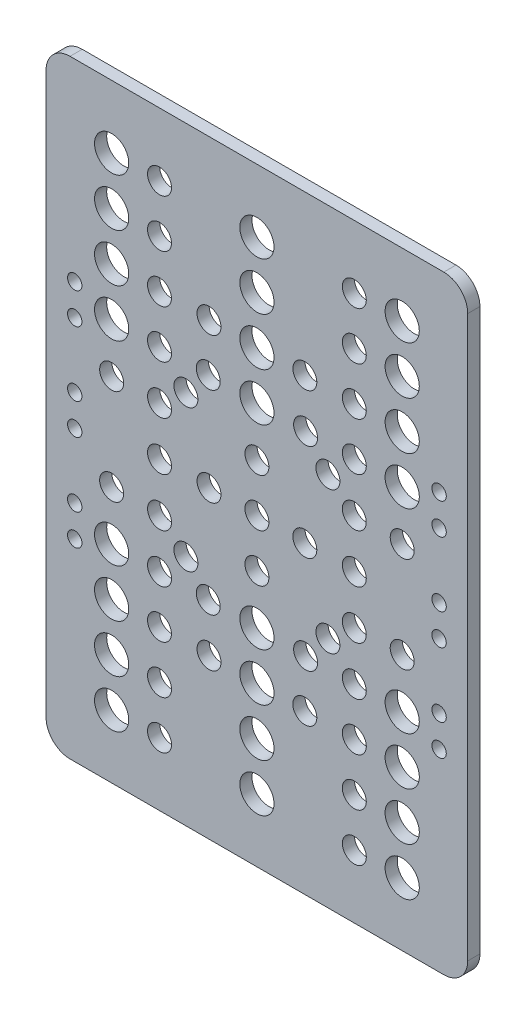
SolidWorks part; units mm, degrees
ref_plane "Front Plane" through (0, 0, 0) normal (0, 0, 1) x (1, 0, 0)
ref_plane "Top Plane" through (0, 0, 0) normal (0, 1, 0) x (1, 0, 0)
ref_plane "Right Plane" through (0, 0, 0) normal (1, 0, 0) x (0, 0, -1)
sketch "Model" plane through (0, 0, 0) normal (0, 0, 1) x (1, 0, 0)
  line L0 (-9.3026, -54.6387) -> (-9.2738, -55.0776)
  line L1 (-9.2738, -54.1979) -> (-9.2738, -55.0776)
  line L2 (-9.2738, -176.2323) -> (-9.2738, -175.3525)
  line L3 (-9.2738, -55.0776) -> (-9.2738, -175.3525)
  line L4 (-9.3026, -175.7915) -> (-9.2738, -175.3525)
  line L5 (-9.3884, -176.2229) -> (-9.3026, -175.7915)
  line L6 (-9.5298, -176.6394) -> (-9.3884, -176.2229)
  line L7 (-9.7243, -177.0339) -> (-9.5298, -176.6394)
  line L8 (-9.9687, -177.3997) -> (-9.7243, -177.0339)
  line L9 (-10.2587, -177.7304) -> (-9.9687, -177.3997)
  line L10 (-10.5895, -178.0204) -> (-10.2587, -177.7304)
  line L11 (-10.9552, -178.2648) -> (-10.5895, -178.0204)
  line L12 (-11.3497, -178.4593) -> (-10.9552, -178.2648)
  line L13 (-11.7662, -178.6007) -> (-11.3497, -178.4593)
  line L14 (-12.1977, -178.6866) -> (-11.7662, -178.6007)
  line L15 (-12.6366, -178.7153) -> (-12.1977, -178.6866)
  line L16 (-11.7569, -178.7153) -> (-12.6366, -178.7153)
  line L17 (-94.7907, -178.7153) -> (-93.911, -178.7153)
  line L18 (-12.6366, -178.7153) -> (-93.911, -178.7153)
  line L19 (-93.911, -178.7153) -> (-94.35, -178.6866)
  line L20 (-94.35, -178.6866) -> (-94.7814, -178.6007)
  line L21 (-94.7814, -178.6007) -> (-95.1979, -178.4593)
  line L22 (-95.1979, -178.4593) -> (-95.5924, -178.2648)
  line L23 (-95.5924, -178.2648) -> (-95.9582, -178.0204)
  line L24 (-95.9582, -178.0204) -> (-96.2889, -177.7304)
  line L25 (-96.2889, -177.7304) -> (-96.5789, -177.3997)
  line L26 (-96.5789, -177.3997) -> (-96.8233, -177.0339)
  line L27 (-96.8233, -177.0339) -> (-97.0178, -176.6394)
  line L28 (-97.0178, -176.6394) -> (-97.1592, -176.2229)
  line L29 (-97.1592, -176.2229) -> (-97.245, -175.7915)
  line L30 (-97.245, -175.7915) -> (-97.2738, -175.3525)
  line L31 (-97.2738, -176.2323) -> (-97.2738, -175.3525)
  line L32 (-97.2738, -54.1979) -> (-97.2738, -55.0776)
  line L33 (-97.2738, -175.3525) -> (-97.2738, -55.0776)
  line L34 (-97.245, -54.6387) -> (-97.2738, -55.0776)
  line L35 (-97.1592, -54.2073) -> (-97.245, -54.6387)
  line L36 (-97.0178, -53.7908) -> (-97.1592, -54.2073)
  line L37 (-96.8233, -53.3962) -> (-97.0178, -53.7908)
  line L38 (-96.5789, -53.0305) -> (-96.8233, -53.3962)
  line L39 (-96.2889, -52.6998) -> (-96.5789, -53.0305)
  line L40 (-95.9582, -52.4098) -> (-96.2889, -52.6998)
  line L41 (-95.5924, -52.1654) -> (-95.9582, -52.4098)
  line L42 (-95.1979, -51.9708) -> (-95.5924, -52.1654)
  line L43 (-94.7814, -51.8294) -> (-95.1979, -51.9708)
  line L44 (-94.35, -51.7436) -> (-94.7814, -51.8294)
  line L45 (-93.911, -51.7148) -> (-94.35, -51.7436)
  line L46 (-11.7569, -51.7148) -> (-12.6366, -51.7148)
  line L47 (-94.7907, -51.7148) -> (-93.911, -51.7148)
  line L48 (-12.6366, -51.7148) -> (-93.911, -51.7148)
  line L49 (-12.6366, -51.7148) -> (-12.1977, -51.7436)
  line L50 (-12.1977, -51.7436) -> (-11.7662, -51.8294)
  line L51 (-11.7662, -51.8294) -> (-11.3497, -51.9708)
  line L52 (-11.3497, -51.9708) -> (-10.9552, -52.1654)
  line L53 (-10.9552, -52.1654) -> (-10.5895, -52.4098)
  line L54 (-10.5895, -52.4098) -> (-10.2587, -52.6998)
  line L55 (-10.2587, -52.6998) -> (-9.9687, -53.0305)
  line L56 (-9.9687, -53.0305) -> (-9.7243, -53.3962)
  line L57 (-9.7243, -53.3962) -> (-9.5298, -53.7907)
  line L58 (-9.5298, -53.7907) -> (-9.3884, -54.2073)
  line L59 (-9.3884, -54.2073) -> (-9.3026, -54.6387)
  line L60 (-20.4305, -62.3715) -> (-19.8634, -63.1106)
  line L61 (-21.1696, -61.8044) -> (-20.4305, -62.3715)
  line L62 (-22.0302, -61.4479) -> (-21.1696, -61.8044)
  line L63 (-22.9538, -61.3263) -> (-22.0302, -61.4479)
  line L64 (-23.8774, -61.4479) -> (-22.9538, -61.3263)
  line L65 (-24.7381, -61.8044) -> (-23.8774, -61.4479)
  line L66 (-25.4771, -62.3715) -> (-24.7381, -61.8044)
  line L67 (-26.0442, -63.1106) -> (-25.4771, -62.3715)
  line L68 (-26.4007, -63.9713) -> (-26.0442, -63.1106)
  line L69 (-26.5223, -64.8948) -> (-26.4007, -63.9713)
  line L70 (-26.4007, -65.8184) -> (-26.5223, -64.8948)
  line L71 (-26.0442, -66.6791) -> (-26.4007, -65.8184)
  line L72 (-25.4771, -67.4182) -> (-26.0442, -66.6791)
  line L73 (-24.7381, -67.9853) -> (-25.4771, -67.4182)
  line L74 (-23.8774, -68.3418) -> (-24.7381, -67.9853)
  line L75 (-22.9538, -68.4633) -> (-23.8774, -68.3418)
  line L76 (-22.0302, -68.3418) -> (-22.9538, -68.4633)
  line L77 (-21.1696, -67.9853) -> (-22.0302, -68.3418)
  line L78 (-20.4305, -67.4182) -> (-21.1696, -67.9853)
  line L79 (-19.8634, -66.6791) -> (-20.4305, -67.4182)
  line L80 (-19.5069, -65.8184) -> (-19.8634, -66.6791)
  line L81 (-19.3853, -64.8948) -> (-19.5069, -65.8184)
  line L82 (-19.5069, -63.9713) -> (-19.3853, -64.8948)
  line L83 (-19.8634, -63.1106) -> (-19.5069, -63.9713)
  line L84 (-85.3616, -163.7671) -> (-84.8438, -163.3698)
  line L85 (-85.7589, -164.2848) -> (-85.3616, -163.7671)
  line L86 (-86.0086, -164.8878) -> (-85.7589, -164.2848)
  line L87 (-86.0938, -165.5348) -> (-86.0086, -164.8878)
  line L88 (-86.0086, -166.1819) -> (-86.0938, -165.5348)
  line L89 (-85.7589, -166.7848) -> (-86.0086, -166.1819)
  line L90 (-85.3616, -167.3026) -> (-85.7589, -166.7848)
  line L91 (-84.8438, -167.6999) -> (-85.3616, -167.3026)
  line L92 (-84.2409, -167.9497) -> (-84.8438, -167.6999)
  line L93 (-83.5938, -168.0348) -> (-84.2409, -167.9497)
  line L94 (-82.9468, -167.9497) -> (-83.5938, -168.0348)
  line L95 (-82.3438, -167.6999) -> (-82.9468, -167.9497)
  line L96 (-81.826, -167.3026) -> (-82.3438, -167.6999)
  line L97 (-81.4287, -166.7848) -> (-81.826, -167.3026)
  line L98 (-81.179, -166.1819) -> (-81.4287, -166.7848)
  line L99 (-81.0938, -165.5348) -> (-81.179, -166.1819)
  line L100 (-81.179, -164.8878) -> (-81.0938, -165.5348)
  line L101 (-81.4287, -164.2848) -> (-81.179, -164.8878)
  line L102 (-81.826, -163.7671) -> (-81.4287, -164.2848)
  line L103 (-82.3438, -163.3698) -> (-81.826, -163.7671)
  line L104 (-82.9468, -163.12) -> (-82.3438, -163.3698)
  line L105 (-83.5938, -163.0348) -> (-82.9468, -163.12)
  line L106 (-84.2409, -163.12) -> (-83.5938, -163.0348)
  line L107 (-84.8438, -163.3698) -> (-84.2409, -163.12)
  line L108 (-82.3438, -153.3698) -> (-81.826, -153.7671)
  line L109 (-82.9468, -153.12) -> (-82.3438, -153.3698)
  line L110 (-83.5938, -153.0348) -> (-82.9468, -153.12)
  line L111 (-84.2409, -153.12) -> (-83.5938, -153.0348)
  line L112 (-84.8438, -153.3698) -> (-84.2409, -153.12)
  line L113 (-85.3616, -153.7671) -> (-84.8438, -153.3698)
  line L114 (-85.7589, -154.2848) -> (-85.3616, -153.7671)
  line L115 (-86.0086, -154.8878) -> (-85.7589, -154.2848)
  line L116 (-86.0938, -155.5348) -> (-86.0086, -154.8878)
  line L117 (-86.0086, -156.1819) -> (-86.0938, -155.5348)
  line L118 (-85.7589, -156.7848) -> (-86.0086, -156.1819)
  line L119 (-85.3616, -157.3026) -> (-85.7589, -156.7848)
  line L120 (-84.8438, -157.6999) -> (-85.3616, -157.3026)
  line L121 (-84.2409, -157.9497) -> (-84.8438, -157.6999)
  line L122 (-83.5938, -158.0348) -> (-84.2409, -157.9497)
  line L123 (-82.9468, -157.9497) -> (-83.5938, -158.0348)
  line L124 (-82.3438, -157.6999) -> (-82.9468, -157.9497)
  line L125 (-81.826, -157.3026) -> (-82.3438, -157.6999)
  line L126 (-81.4287, -156.7848) -> (-81.826, -157.3026)
  line L127 (-81.179, -156.1819) -> (-81.4287, -156.7848)
  line L128 (-81.0938, -155.5348) -> (-81.179, -156.1819)
  line L129 (-81.179, -154.8878) -> (-81.0938, -155.5348)
  line L130 (-81.4287, -154.2848) -> (-81.179, -154.8878)
  line L131 (-81.826, -153.7671) -> (-81.4287, -154.2848)
  line L132 (-40.9438, -93.6448) -> (-40.6941, -94.2478)
  line L133 (-41.3411, -93.1271) -> (-40.9438, -93.6448)
  line L134 (-41.8589, -92.7298) -> (-41.3411, -93.1271)
  line L135 (-42.4619, -92.48) -> (-41.8589, -92.7298)
  line L136 (-43.1089, -92.3948) -> (-42.4619, -92.48)
  line L137 (-43.756, -92.48) -> (-43.1089, -92.3948)
  line L138 (-44.3589, -92.7298) -> (-43.756, -92.48)
  line L139 (-44.8767, -93.1271) -> (-44.3589, -92.7298)
  line L140 (-45.274, -93.6448) -> (-44.8767, -93.1271)
  line L141 (-45.5237, -94.2478) -> (-45.274, -93.6448)
  line L142 (-45.6089, -94.8948) -> (-45.5237, -94.2478)
  line L143 (-45.5237, -95.5419) -> (-45.6089, -94.8948)
  line L144 (-45.274, -96.1448) -> (-45.5237, -95.5419)
  line L145 (-44.8767, -96.6626) -> (-45.274, -96.1448)
  line L146 (-44.3589, -97.0599) -> (-44.8767, -96.6626)
  line L147 (-43.756, -97.3097) -> (-44.3589, -97.0599)
  line L148 (-43.1089, -97.3948) -> (-43.756, -97.3097)
  line L149 (-42.4619, -97.3097) -> (-43.1089, -97.3948)
  line L150 (-41.8589, -97.0599) -> (-42.4619, -97.3097)
  line L151 (-41.3411, -96.6626) -> (-41.8589, -97.0599)
  line L152 (-40.9438, -96.1448) -> (-41.3411, -96.6626)
  line L153 (-40.6941, -95.5419) -> (-40.9438, -96.1448)
  line L154 (-40.6089, -94.8948) -> (-40.6941, -95.5419)
  line L155 (-40.6941, -94.2478) -> (-40.6089, -94.8948)
  line L156 (-75.3616, -123.6076) -> (-74.8438, -123.2103)
  line L157 (-75.7589, -124.1253) -> (-75.3616, -123.6076)
  line L158 (-76.0086, -124.7283) -> (-75.7589, -124.1253)
  line L159 (-76.0938, -125.3753) -> (-76.0086, -124.7283)
  line L160 (-76.0086, -126.0224) -> (-76.0938, -125.3753)
  line L161 (-75.7589, -126.6253) -> (-76.0086, -126.0224)
  line L162 (-75.3616, -127.1431) -> (-75.7589, -126.6253)
  line L163 (-74.8438, -127.5404) -> (-75.3616, -127.1431)
  line L164 (-74.2409, -127.7901) -> (-74.8438, -127.5404)
  line L165 (-73.5938, -127.8753) -> (-74.2409, -127.7901)
  line L166 (-72.9468, -127.7901) -> (-73.5938, -127.8753)
  line L167 (-72.3438, -127.5404) -> (-72.9468, -127.7901)
  line L168 (-71.826, -127.1431) -> (-72.3438, -127.5404)
  line L169 (-71.4287, -126.6253) -> (-71.826, -127.1431)
  line L170 (-71.179, -126.0224) -> (-71.4287, -126.6253)
  line L171 (-71.0938, -125.3753) -> (-71.179, -126.0224)
  line L172 (-71.179, -124.7283) -> (-71.0938, -125.3753)
  line L173 (-71.4287, -124.1253) -> (-71.179, -124.7283)
  line L174 (-71.826, -123.6076) -> (-71.4287, -124.1253)
  line L175 (-72.3438, -123.2103) -> (-71.826, -123.6076)
  line L176 (-72.9468, -122.9605) -> (-72.3438, -123.2103)
  line L177 (-73.5938, -122.8753) -> (-72.9468, -122.9605)
  line L178 (-74.2409, -122.9605) -> (-73.5938, -122.8753)
  line L179 (-74.8438, -123.2103) -> (-74.2409, -122.9605)
  line L180 (-65.8486, -134.8878) -> (-65.5989, -134.2848)
  line L181 (-65.9338, -135.5348) -> (-65.8486, -134.8878)
  line L182 (-65.8486, -136.1819) -> (-65.9338, -135.5348)
  line L183 (-65.5989, -136.7848) -> (-65.8486, -136.1819)
  line L184 (-65.2016, -137.3026) -> (-65.5989, -136.7848)
  line L185 (-64.6838, -137.6999) -> (-65.2016, -137.3026)
  line L186 (-64.0809, -137.9497) -> (-64.6838, -137.6999)
  line L187 (-63.4338, -138.0348) -> (-64.0809, -137.9497)
  line L188 (-62.7868, -137.9497) -> (-63.4338, -138.0348)
  line L189 (-62.1838, -137.6999) -> (-62.7868, -137.9497)
  line L190 (-61.666, -137.3026) -> (-62.1838, -137.6999)
  line L191 (-61.2687, -136.7848) -> (-61.666, -137.3026)
  line L192 (-61.019, -136.1819) -> (-61.2687, -136.7848)
  line L193 (-60.9338, -135.5348) -> (-61.019, -136.1819)
  line L194 (-61.019, -134.8878) -> (-60.9338, -135.5348)
  line L195 (-61.2687, -134.2848) -> (-61.019, -134.8878)
  line L196 (-61.666, -133.7671) -> (-61.2687, -134.2848)
  line L197 (-62.1838, -133.3698) -> (-61.666, -133.7671)
  line L198 (-62.7868, -133.12) -> (-62.1838, -133.3698)
  line L199 (-63.4338, -133.0348) -> (-62.7868, -133.12)
  line L200 (-64.0809, -133.12) -> (-63.4338, -133.0348)
  line L201 (-64.6838, -133.3698) -> (-64.0809, -133.12)
  line L202 (-65.2016, -133.7671) -> (-64.6838, -133.3698)
  line L203 (-65.5989, -134.2848) -> (-65.2016, -133.7671)
  line L204 (-63.4338, -92.3949) -> (-62.7868, -92.48)
  line L205 (-64.0809, -92.48) -> (-63.4338, -92.3949)
  line L206 (-64.6838, -92.7298) -> (-64.0809, -92.48)
  line L207 (-65.2016, -93.1271) -> (-64.6838, -92.7298)
  line L208 (-65.5989, -93.6449) -> (-65.2016, -93.1271)
  line L209 (-65.8486, -94.2478) -> (-65.5989, -93.6449)
  line L210 (-65.9338, -94.8949) -> (-65.8486, -94.2478)
  line L211 (-65.8486, -95.5419) -> (-65.9338, -94.8949)
  line L212 (-65.5989, -96.1449) -> (-65.8486, -95.5419)
  line L213 (-65.2016, -96.6626) -> (-65.5989, -96.1449)
  line L214 (-64.6838, -97.0599) -> (-65.2016, -96.6626)
  line L215 (-64.0809, -97.3097) -> (-64.6838, -97.0599)
  line L216 (-63.4338, -97.3949) -> (-64.0809, -97.3097)
  line L217 (-62.7868, -97.3097) -> (-63.4338, -97.3949)
  line L218 (-62.1838, -97.0599) -> (-62.7868, -97.3097)
  line L219 (-61.666, -96.6626) -> (-62.1838, -97.0599)
  line L220 (-61.2687, -96.1449) -> (-61.666, -96.6626)
  line L221 (-61.019, -95.5419) -> (-61.2687, -96.1449)
  line L222 (-60.9338, -94.8949) -> (-61.019, -95.5419)
  line L223 (-61.019, -94.2478) -> (-60.9338, -94.8949)
  line L224 (-61.2687, -93.6449) -> (-61.019, -94.2478)
  line L225 (-61.666, -93.1271) -> (-61.2687, -93.6449)
  line L226 (-62.1838, -92.7298) -> (-61.666, -93.1271)
  line L227 (-62.7868, -92.48) -> (-62.1838, -92.7298)
  line L228 (-35.3686, -126.0224) -> (-35.4538, -125.3753)
  line L229 (-35.1189, -126.6253) -> (-35.3686, -126.0224)
  line L230 (-34.7216, -127.1431) -> (-35.1189, -126.6253)
  line L231 (-34.2038, -127.5404) -> (-34.7216, -127.1431)
  line L232 (-33.6009, -127.7901) -> (-34.2038, -127.5404)
  line L233 (-32.9538, -127.8753) -> (-33.6009, -127.7901)
  line L234 (-32.3068, -127.7901) -> (-32.9538, -127.8753)
  line L235 (-31.7038, -127.5404) -> (-32.3068, -127.7901)
  line L236 (-31.186, -127.1431) -> (-31.7038, -127.5404)
  line L237 (-30.7887, -126.6253) -> (-31.186, -127.1431)
  line L238 (-30.539, -126.0224) -> (-30.7887, -126.6253)
  line L239 (-30.4538, -125.3753) -> (-30.539, -126.0224)
  line L240 (-30.539, -124.7283) -> (-30.4538, -125.3753)
  line L241 (-30.7887, -124.1253) -> (-30.539, -124.7283)
  line L242 (-31.186, -123.6076) -> (-30.7887, -124.1253)
  line L243 (-31.7038, -123.2103) -> (-31.186, -123.6076)
  line L244 (-32.3068, -122.9605) -> (-31.7038, -123.2103)
  line L245 (-32.9538, -122.8753) -> (-32.3068, -122.9605)
  line L246 (-33.6009, -122.9605) -> (-32.9538, -122.8753)
  line L247 (-34.2038, -123.2103) -> (-33.6009, -122.9605)
  line L248 (-34.7216, -123.6076) -> (-34.2038, -123.2103)
  line L249 (-35.1189, -124.1253) -> (-34.7216, -123.6076)
  line L250 (-35.3686, -124.7283) -> (-35.1189, -124.1253)
  line L251 (-35.4538, -125.3753) -> (-35.3686, -124.7283)
  line L252 (-71.179, -104.4034) -> (-71.0938, -105.0504)
  line L253 (-71.4287, -103.8004) -> (-71.179, -104.4034)
  line L254 (-71.826, -103.2827) -> (-71.4287, -103.8004)
  line L255 (-72.3438, -102.8854) -> (-71.826, -103.2827)
  line L256 (-72.9468, -102.6356) -> (-72.3438, -102.8854)
  line L257 (-73.5938, -102.5504) -> (-72.9468, -102.6356)
  line L258 (-74.2409, -102.6356) -> (-73.5938, -102.5504)
  line L259 (-74.8438, -102.8854) -> (-74.2409, -102.6356)
  line L260 (-75.3616, -103.2827) -> (-74.8438, -102.8854)
  line L261 (-75.7589, -103.8004) -> (-75.3616, -103.2827)
  line L262 (-76.0086, -104.4034) -> (-75.7589, -103.8004)
  line L263 (-76.0938, -105.0504) -> (-76.0086, -104.4034)
  line L264 (-76.0086, -105.6975) -> (-76.0938, -105.0504)
  line L265 (-75.7589, -106.3004) -> (-76.0086, -105.6975)
  line L266 (-75.3616, -106.8182) -> (-75.7589, -106.3004)
  line L267 (-74.8438, -107.2155) -> (-75.3616, -106.8182)
  line L268 (-74.2409, -107.4652) -> (-74.8438, -107.2155)
  line L269 (-73.5938, -107.5504) -> (-74.2409, -107.4652)
  line L270 (-72.9468, -107.4652) -> (-73.5938, -107.5504)
  line L271 (-72.3438, -107.2155) -> (-72.9468, -107.4652)
  line L272 (-71.826, -106.8182) -> (-72.3438, -107.2155)
  line L273 (-71.4287, -106.3004) -> (-71.826, -106.8182)
  line L274 (-71.179, -105.6975) -> (-71.4287, -106.3004)
  line L275 (-71.0938, -105.0504) -> (-71.179, -105.6975)
  line L276 (-35.1137, -103.8027) -> (-34.7164, -103.2849)
  line L277 (-35.3634, -104.4056) -> (-35.1137, -103.8027)
  line L278 (-35.4486, -105.0527) -> (-35.3634, -104.4056)
  line L279 (-35.3634, -105.6997) -> (-35.4486, -105.0527)
  line L280 (-35.1137, -106.3027) -> (-35.3634, -105.6997)
  line L281 (-34.7164, -106.8204) -> (-35.1137, -106.3027)
  line L282 (-34.1986, -107.2177) -> (-34.7164, -106.8204)
  line L283 (-33.5957, -107.4675) -> (-34.1986, -107.2177)
  line L284 (-32.9486, -107.5527) -> (-33.5957, -107.4675)
  line L285 (-32.3016, -107.4675) -> (-32.9486, -107.5527)
  line L286 (-31.6986, -107.2177) -> (-32.3016, -107.4675)
  line L287 (-31.1809, -106.8204) -> (-31.6986, -107.2177)
  line L288 (-30.7836, -106.3027) -> (-31.1809, -106.8204)
  line L289 (-30.5338, -105.6997) -> (-30.7836, -106.3027)
  line L290 (-30.4486, -105.0527) -> (-30.5338, -105.6997)
  line L291 (-30.5338, -104.4056) -> (-30.4486, -105.0527)
  line L292 (-30.7836, -103.8027) -> (-30.5338, -104.4056)
  line L293 (-31.1809, -103.2849) -> (-30.7836, -103.8027)
  line L294 (-31.6986, -102.8876) -> (-31.1809, -103.2849)
  line L295 (-32.3016, -102.6379) -> (-31.6986, -102.8876)
  line L296 (-32.9486, -102.5527) -> (-32.3016, -102.6379)
  line L297 (-33.5957, -102.6379) -> (-32.9486, -102.5527)
  line L298 (-34.1986, -102.8876) -> (-33.5957, -102.6379)
  line L299 (-34.7164, -103.2849) -> (-34.1986, -102.8876)
  line L300 (-42.4619, -133.12) -> (-41.8589, -133.3698)
  line L301 (-43.1089, -133.0348) -> (-42.4619, -133.12)
  line L302 (-43.756, -133.12) -> (-43.1089, -133.0348)
  line L303 (-44.3589, -133.3698) -> (-43.756, -133.12)
  line L304 (-44.8767, -133.7671) -> (-44.3589, -133.3698)
  line L305 (-45.274, -134.2848) -> (-44.8767, -133.7671)
  line L306 (-45.5237, -134.8878) -> (-45.274, -134.2848)
  line L307 (-45.6089, -135.5348) -> (-45.5237, -134.8878)
  line L308 (-45.5237, -136.1819) -> (-45.6089, -135.5348)
  line L309 (-45.274, -136.7848) -> (-45.5237, -136.1819)
  line L310 (-44.8767, -137.3026) -> (-45.274, -136.7848)
  line L311 (-44.3589, -137.6999) -> (-44.8767, -137.3026)
  line L312 (-43.756, -137.9497) -> (-44.3589, -137.6999)
  line L313 (-43.1089, -138.0348) -> (-43.756, -137.9497)
  line L314 (-42.4619, -137.9497) -> (-43.1089, -138.0348)
  line L315 (-41.8589, -137.6999) -> (-42.4619, -137.9497)
  line L316 (-41.3411, -137.3026) -> (-41.8589, -137.6999)
  line L317 (-40.9438, -136.7848) -> (-41.3411, -137.3026)
  line L318 (-40.6941, -136.1819) -> (-40.9438, -136.7848)
  line L319 (-40.6089, -135.5348) -> (-40.6941, -136.1819)
  line L320 (-40.6941, -134.8878) -> (-40.6089, -135.5348)
  line L321 (-40.9438, -134.2848) -> (-40.6941, -134.8878)
  line L322 (-41.3411, -133.7671) -> (-40.9438, -134.2848)
  line L323 (-41.8589, -133.3698) -> (-41.3411, -133.7671)
  line L324 (-40.7738, -145.5348) -> (-40.859, -146.1819)
  line L325 (-40.859, -144.8878) -> (-40.7738, -145.5348)
  line L326 (-41.1087, -144.2848) -> (-40.859, -144.8878)
  line L327 (-41.506, -143.7671) -> (-41.1087, -144.2848)
  line L328 (-42.0238, -143.3698) -> (-41.506, -143.7671)
  line L329 (-42.6268, -143.12) -> (-42.0238, -143.3698)
  line L330 (-43.2738, -143.0348) -> (-42.6268, -143.12)
  line L331 (-43.9209, -143.12) -> (-43.2738, -143.0348)
  line L332 (-44.5238, -143.3698) -> (-43.9209, -143.12)
  line L333 (-45.0416, -143.7671) -> (-44.5238, -143.3698)
  line L334 (-45.4389, -144.2848) -> (-45.0416, -143.7671)
  line L335 (-45.6886, -144.8878) -> (-45.4389, -144.2848)
  line L336 (-45.7738, -145.5348) -> (-45.6886, -144.8878)
  line L337 (-45.6886, -146.1819) -> (-45.7738, -145.5348)
  line L338 (-45.4389, -146.7848) -> (-45.6886, -146.1819)
  line L339 (-45.0416, -147.3026) -> (-45.4389, -146.7848)
  line L340 (-44.5238, -147.6999) -> (-45.0416, -147.3026)
  line L341 (-43.9209, -147.9497) -> (-44.5238, -147.6999)
  line L342 (-43.2738, -148.0348) -> (-43.9209, -147.9497)
  line L343 (-42.6268, -147.9497) -> (-43.2738, -148.0348)
  line L344 (-42.0238, -147.6999) -> (-42.6268, -147.9497)
  line L345 (-41.506, -147.3026) -> (-42.0238, -147.6999)
  line L346 (-41.1087, -146.7848) -> (-41.506, -147.3026)
  line L347 (-40.859, -146.1819) -> (-41.1087, -146.7848)
  line L348 (-37.2038, -132.2048) -> (-37.8068, -132.4546)
  line L349 (-36.686, -131.8075) -> (-37.2038, -132.2048)
  line L350 (-36.2887, -131.2897) -> (-36.686, -131.8075)
  line L351 (-36.039, -130.6868) -> (-36.2887, -131.2897)
  line L352 (-35.9538, -130.0397) -> (-36.039, -130.6868)
  line L353 (-36.039, -129.3927) -> (-35.9538, -130.0397)
  line L354 (-36.2887, -128.7897) -> (-36.039, -129.3927)
  line L355 (-36.686, -128.272) -> (-36.2887, -128.7897)
  line L356 (-37.2038, -127.8747) -> (-36.686, -128.272)
  line L357 (-37.8068, -127.6249) -> (-37.2038, -127.8747)
  line L358 (-38.4538, -127.5397) -> (-37.8068, -127.6249)
  line L359 (-39.1009, -127.6249) -> (-38.4538, -127.5397)
  line L360 (-39.7038, -127.8747) -> (-39.1009, -127.6249)
  line L361 (-40.2216, -128.272) -> (-39.7038, -127.8747)
  line L362 (-40.6189, -128.7897) -> (-40.2216, -128.272)
  line L363 (-40.8686, -129.3927) -> (-40.6189, -128.7897)
  line L364 (-40.9538, -130.0397) -> (-40.8686, -129.3927)
  line L365 (-40.8686, -130.6868) -> (-40.9538, -130.0397)
  line L366 (-40.6189, -131.2897) -> (-40.8686, -130.6868)
  line L367 (-40.2216, -131.8075) -> (-40.6189, -131.2897)
  line L368 (-39.7038, -132.2048) -> (-40.2216, -131.8075)
  line L369 (-39.1009, -132.4546) -> (-39.7038, -132.2048)
  line L370 (-38.4538, -132.5397) -> (-39.1009, -132.4546)
  line L371 (-37.8068, -132.4546) -> (-38.4538, -132.5397)
  line L372 (-13.7538, -111.0854) -> (-13.7538, -111.9651)
  line L373 (-13.7538, -119.3448) -> (-13.7538, -118.4651)
  line L374 (-13.7538, -111.9651) -> (-13.7538, -118.4651)
  line L375 (-13.8049, -111.5769) -> (-13.7538, -111.9651)
  line L376 (-13.9548, -111.2151) -> (-13.8049, -111.5769)
  line L377 (-14.1932, -110.9045) -> (-13.9548, -111.2151)
  line L378 (-14.5038, -110.6661) -> (-14.1932, -110.9045)
  line L379 (-14.8656, -110.5162) -> (-14.5038, -110.6661)
  line L380 (-15.2538, -110.4651) -> (-14.8656, -110.5162)
  line L381 (-15.642, -110.5162) -> (-15.2538, -110.4651)
  line L382 (-16.0038, -110.6661) -> (-15.642, -110.5162)
  line L383 (-16.3145, -110.9045) -> (-16.0038, -110.6661)
  line L384 (-16.5528, -111.2151) -> (-16.3145, -110.9045)
  line L385 (-16.7027, -111.5769) -> (-16.5528, -111.2151)
  line L386 (-16.7538, -111.9651) -> (-16.7027, -111.5769)
  line L387 (-16.7538, -119.3448) -> (-16.7538, -118.4651)
  line L388 (-16.7538, -111.0854) -> (-16.7538, -111.9651)
  line L389 (-16.7538, -118.4651) -> (-16.7538, -111.9651)
  line L390 (-16.7027, -118.8533) -> (-16.7538, -118.4651)
  line L391 (-16.5528, -119.2151) -> (-16.7027, -118.8533)
  line L392 (-16.3145, -119.5258) -> (-16.5528, -119.2151)
  line L393 (-16.0038, -119.7641) -> (-16.3145, -119.5258)
  line L394 (-15.642, -119.914) -> (-16.0038, -119.7641)
  line L395 (-15.2538, -119.9651) -> (-15.642, -119.914)
  line L396 (-14.8656, -119.914) -> (-15.2538, -119.9651)
  line L397 (-14.5038, -119.7641) -> (-14.8656, -119.914)
  line L398 (-14.1932, -119.5258) -> (-14.5038, -119.7641)
  line L399 (-13.9548, -119.2151) -> (-14.1932, -119.5258)
  line L400 (-13.8049, -118.8533) -> (-13.9548, -119.2151)
  line L401 (-13.7538, -118.4651) -> (-13.8049, -118.8533)
  line L402 (-69.3438, -127.8747) -> (-68.7409, -127.6249)
  line L403 (-69.8616, -128.272) -> (-69.3438, -127.8747)
  line L404 (-70.2589, -128.7898) -> (-69.8616, -128.272)
  line L405 (-70.5086, -129.3927) -> (-70.2589, -128.7898)
  line L406 (-70.5938, -130.0398) -> (-70.5086, -129.3927)
  line L407 (-70.5086, -130.6868) -> (-70.5938, -130.0398)
  line L408 (-70.2589, -131.2898) -> (-70.5086, -130.6868)
  line L409 (-69.8616, -131.8075) -> (-70.2589, -131.2898)
  line L410 (-69.3438, -132.2048) -> (-69.8616, -131.8075)
  line L411 (-68.7409, -132.4546) -> (-69.3438, -132.2048)
  line L412 (-68.0938, -132.5398) -> (-68.7409, -132.4546)
  line L413 (-67.4468, -132.4546) -> (-68.0938, -132.5398)
  line L414 (-66.8438, -132.2048) -> (-67.4468, -132.4546)
  line L415 (-66.326, -131.8075) -> (-66.8438, -132.2048)
  line L416 (-65.9287, -131.2898) -> (-66.326, -131.8075)
  line L417 (-65.679, -130.6868) -> (-65.9287, -131.2898)
  line L418 (-65.5938, -130.0398) -> (-65.679, -130.6868)
  line L419 (-65.679, -129.3927) -> (-65.5938, -130.0398)
  line L420 (-65.9287, -128.7898) -> (-65.679, -129.3927)
  line L421 (-66.326, -128.272) -> (-65.9287, -128.7898)
  line L422 (-66.8438, -127.8747) -> (-66.326, -128.272)
  line L423 (-67.4468, -127.6249) -> (-66.8438, -127.8747)
  line L424 (-68.0938, -127.5398) -> (-67.4468, -127.6249)
  line L425 (-68.7409, -127.6249) -> (-68.0938, -127.5398)
  line L426 (-69.8616, -98.6222) -> (-69.3438, -98.2249)
  line L427 (-70.2589, -99.1399) -> (-69.8616, -98.6222)
  line L428 (-70.5086, -99.7429) -> (-70.2589, -99.1399)
  line L429 (-70.5938, -100.3899) -> (-70.5086, -99.7429)
  line L430 (-70.5086, -101.037) -> (-70.5938, -100.3899)
  line L431 (-70.2589, -101.6399) -> (-70.5086, -101.037)
  line L432 (-69.8616, -102.1577) -> (-70.2589, -101.6399)
  line L433 (-69.3438, -102.555) -> (-69.8616, -102.1577)
  line L434 (-68.7409, -102.8048) -> (-69.3438, -102.555)
  line L435 (-68.0938, -102.8899) -> (-68.7409, -102.8048)
  line L436 (-67.4468, -102.8048) -> (-68.0938, -102.8899)
  line L437 (-66.8438, -102.555) -> (-67.4468, -102.8048)
  line L438 (-66.326, -102.1577) -> (-66.8438, -102.555)
  line L439 (-65.9287, -101.6399) -> (-66.326, -102.1577)
  line L440 (-65.679, -101.037) -> (-65.9287, -101.6399)
  line L441 (-65.5938, -100.3899) -> (-65.679, -101.037)
  line L442 (-65.679, -99.7429) -> (-65.5938, -100.3899)
  line L443 (-65.9287, -99.1399) -> (-65.679, -99.7429)
  line L444 (-66.326, -98.6222) -> (-65.9287, -99.1399)
  line L445 (-66.8438, -98.2249) -> (-66.326, -98.6222)
  line L446 (-67.4468, -97.9751) -> (-66.8438, -98.2249)
  line L447 (-68.0938, -97.8899) -> (-67.4468, -97.9751)
  line L448 (-68.7409, -97.9751) -> (-68.0938, -97.8899)
  line L449 (-69.3438, -98.2249) -> (-68.7409, -97.9751)
  line L450 (-92.7427, -111.5769) -> (-92.7938, -111.9651)
  line L451 (-92.7938, -111.0854) -> (-92.7938, -111.9651)
  line L452 (-92.7938, -119.3448) -> (-92.7938, -118.4651)
  line L453 (-92.7938, -111.9651) -> (-92.7938, -118.4651)
  line L454 (-92.7938, -118.4651) -> (-92.7427, -118.8533)
  line L455 (-92.7427, -118.8533) -> (-92.5928, -119.2151)
  line L456 (-92.5928, -119.2151) -> (-92.3545, -119.5257)
  line L457 (-92.3545, -119.5257) -> (-92.0438, -119.7641)
  line L458 (-92.0438, -119.7641) -> (-91.6821, -119.914)
  line L459 (-91.6821, -119.914) -> (-91.2938, -119.9651)
  line L460 (-91.2938, -119.9651) -> (-90.9056, -119.914)
  line L461 (-90.9056, -119.914) -> (-90.5438, -119.7641)
  line L462 (-90.5438, -119.7641) -> (-90.2332, -119.5257)
  line L463 (-90.2332, -119.5257) -> (-89.9948, -119.2151)
  line L464 (-89.9948, -119.2151) -> (-89.8449, -118.8533)
  line L465 (-89.8449, -118.8533) -> (-89.7938, -118.4651)
  line L466 (-89.7938, -119.3448) -> (-89.7938, -118.4651)
  line L467 (-89.7938, -111.0854) -> (-89.7938, -111.9651)
  line L468 (-89.7938, -118.4651) -> (-89.7938, -111.9651)
  line L469 (-89.7938, -111.9651) -> (-89.8449, -111.5769)
  line L470 (-89.8449, -111.5769) -> (-89.9948, -111.2151)
  line L471 (-89.9948, -111.2151) -> (-90.2332, -110.9045)
  line L472 (-90.2332, -110.9045) -> (-90.5438, -110.6661)
  line L473 (-90.5438, -110.6661) -> (-90.9056, -110.5162)
  line L474 (-90.9056, -110.5162) -> (-91.2938, -110.4651)
  line L475 (-91.2938, -110.4651) -> (-91.6821, -110.5162)
  line L476 (-91.6821, -110.5162) -> (-92.0438, -110.6661)
  line L477 (-92.0438, -110.6661) -> (-92.3545, -110.9045)
  line L478 (-92.3545, -110.9045) -> (-92.5928, -111.2151)
  line L479 (-92.5928, -111.2151) -> (-92.7427, -111.5769)
  line L480 (-22.3068, -143.12) -> (-21.7038, -143.3698)
  line L481 (-22.9538, -143.0348) -> (-22.3068, -143.12)
  line L482 (-23.6009, -143.12) -> (-22.9538, -143.0348)
  line L483 (-24.2038, -143.3698) -> (-23.6009, -143.12)
  line L484 (-24.7216, -143.7671) -> (-24.2038, -143.3698)
  line L485 (-25.1189, -144.2848) -> (-24.7216, -143.7671)
  line L486 (-25.3686, -144.8878) -> (-25.1189, -144.2848)
  line L487 (-25.4538, -145.5348) -> (-25.3686, -144.8878)
  line L488 (-25.3686, -146.1819) -> (-25.4538, -145.5348)
  line L489 (-25.1189, -146.7848) -> (-25.3686, -146.1819)
  line L490 (-24.7216, -147.3026) -> (-25.1189, -146.7848)
  line L491 (-24.2038, -147.6999) -> (-24.7216, -147.3026)
  line L492 (-23.6009, -147.9497) -> (-24.2038, -147.6999)
  line L493 (-22.9538, -148.0348) -> (-23.6009, -147.9497)
  line L494 (-22.3068, -147.9497) -> (-22.9538, -148.0348)
  line L495 (-21.7038, -147.6999) -> (-22.3068, -147.9497)
  line L496 (-21.186, -147.3026) -> (-21.7038, -147.6999)
  line L497 (-20.7887, -146.7848) -> (-21.186, -147.3026)
  line L498 (-20.539, -146.1819) -> (-20.7887, -146.7848)
  line L499 (-20.4538, -145.5348) -> (-20.539, -146.1819)
  line L500 (-20.539, -144.8878) -> (-20.4538, -145.5348)
  line L501 (-20.7887, -144.2848) -> (-20.539, -144.8878)
  line L502 (-21.186, -143.7671) -> (-20.7887, -144.2848)
  line L503 (-21.7038, -143.3698) -> (-21.186, -143.7671)
  line L504 (-75.3665, -86.6626) -> (-75.7638, -86.1448)
  line L505 (-74.8487, -87.0599) -> (-75.3665, -86.6626)
  line L506 (-74.2458, -87.3097) -> (-74.8487, -87.0599)
  line L507 (-73.5987, -87.3948) -> (-74.2458, -87.3097)
  line L508 (-72.9517, -87.3097) -> (-73.5987, -87.3948)
  line L509 (-72.3487, -87.0599) -> (-72.9517, -87.3097)
  line L510 (-71.8309, -86.6626) -> (-72.3487, -87.0599)
  line L511 (-71.4337, -86.1448) -> (-71.8309, -86.6626)
  line L512 (-71.1839, -85.5419) -> (-71.4337, -86.1448)
  line L513 (-71.0987, -84.8948) -> (-71.1839, -85.5419)
  line L514 (-71.1839, -84.2478) -> (-71.0987, -84.8948)
  line L515 (-71.4337, -83.6448) -> (-71.1839, -84.2478)
  line L516 (-71.8309, -83.1271) -> (-71.4337, -83.6448)
  line L517 (-72.3487, -82.7298) -> (-71.8309, -83.1271)
  line L518 (-72.9517, -82.48) -> (-72.3487, -82.7298)
  line L519 (-73.5987, -82.3948) -> (-72.9517, -82.48)
  line L520 (-74.2458, -82.48) -> (-73.5987, -82.3948)
  line L521 (-74.8487, -82.7298) -> (-74.2458, -82.48)
  line L522 (-75.3665, -83.1271) -> (-74.8487, -82.7298)
  line L523 (-75.7638, -83.6448) -> (-75.3665, -83.1271)
  line L524 (-76.0135, -84.2478) -> (-75.7638, -83.6448)
  line L525 (-76.0987, -84.8948) -> (-76.0135, -84.2478)
  line L526 (-76.0135, -85.5419) -> (-76.0987, -84.8948)
  line L527 (-75.7638, -86.1448) -> (-76.0135, -85.5419)
  line L528 (-89.7938, -91.9651) -> (-89.8449, -91.5769)
  line L529 (-89.8449, -91.5769) -> (-89.9948, -91.2151)
  line L530 (-89.9948, -91.2151) -> (-90.2332, -90.9045)
  line L531 (-90.2332, -90.9045) -> (-90.5438, -90.6661)
  line L532 (-90.5438, -90.6661) -> (-90.9056, -90.5162)
  line L533 (-90.9056, -90.5162) -> (-91.2938, -90.4651)
  line L534 (-91.2938, -90.4651) -> (-91.6821, -90.5162)
  line L535 (-91.6821, -90.5162) -> (-92.0438, -90.6661)
  line L536 (-92.0438, -90.6661) -> (-92.3545, -90.9045)
  line L537 (-92.3545, -90.9045) -> (-92.5928, -91.2151)
  line L538 (-92.5928, -91.2151) -> (-92.7427, -91.5769)
  line L539 (-92.7427, -91.5769) -> (-92.7938, -91.9651)
  line L540 (-92.7938, -91.0854) -> (-92.7938, -91.9651)
  line L541 (-92.7938, -99.3448) -> (-92.7938, -98.4651)
  line L542 (-92.7938, -91.9651) -> (-92.7938, -98.4651)
  line L543 (-92.7938, -98.4651) -> (-92.7427, -98.8533)
  line L544 (-92.7427, -98.8533) -> (-92.5928, -99.2151)
  line L545 (-92.5928, -99.2151) -> (-92.3545, -99.5257)
  line L546 (-92.3545, -99.5257) -> (-92.0438, -99.7641)
  line L547 (-92.0438, -99.7641) -> (-91.6821, -99.914)
  line L548 (-91.6821, -99.914) -> (-91.2938, -99.9651)
  line L549 (-91.2938, -99.9651) -> (-90.9056, -99.914)
  line L550 (-90.9056, -99.914) -> (-90.5438, -99.7641)
  line L551 (-90.5438, -99.7641) -> (-90.2332, -99.5257)
  line L552 (-90.2332, -99.5257) -> (-89.9948, -99.2151)
  line L553 (-89.9948, -99.2151) -> (-89.8449, -98.8533)
  line L554 (-89.8449, -98.8533) -> (-89.7938, -98.4651)
  line L555 (-89.7938, -99.3448) -> (-89.7938, -98.4651)
  line L556 (-89.7938, -91.0854) -> (-89.7938, -91.9651)
  line L557 (-89.7938, -98.4651) -> (-89.7938, -91.9651)
  line L558 (-52.3502, -61.4479) -> (-51.4896, -61.8044)
  line L559 (-53.2738, -61.3263) -> (-52.3502, -61.4479)
  line L560 (-54.1974, -61.4479) -> (-53.2738, -61.3263)
  line L561 (-55.0581, -61.8044) -> (-54.1974, -61.4479)
  line L562 (-55.7971, -62.3715) -> (-55.0581, -61.8044)
  line L563 (-56.3642, -63.1106) -> (-55.7971, -62.3715)
  line L564 (-56.7207, -63.9713) -> (-56.3642, -63.1106)
  line L565 (-56.8423, -64.8948) -> (-56.7207, -63.9713)
  line L566 (-56.7207, -65.8184) -> (-56.8423, -64.8948)
  line L567 (-56.3642, -66.6791) -> (-56.7207, -65.8184)
  line L568 (-55.7971, -67.4182) -> (-56.3642, -66.6791)
  line L569 (-55.0581, -67.9853) -> (-55.7971, -67.4182)
  line L570 (-54.1974, -68.3418) -> (-55.0581, -67.9853)
  line L571 (-53.2738, -68.4633) -> (-54.1974, -68.3418)
  line L572 (-52.3502, -68.3418) -> (-53.2738, -68.4633)
  line L573 (-51.4896, -67.9853) -> (-52.3502, -68.3418)
  line L574 (-50.7505, -67.4182) -> (-51.4896, -67.9853)
  line L575 (-50.1834, -66.6791) -> (-50.7505, -67.4182)
  line L576 (-49.8269, -65.8184) -> (-50.1834, -66.6791)
  line L577 (-49.7053, -64.8948) -> (-49.8269, -65.8184)
  line L578 (-49.8269, -63.9713) -> (-49.7053, -64.8948)
  line L579 (-50.1834, -63.1106) -> (-49.8269, -63.9713)
  line L580 (-50.7505, -62.3715) -> (-50.1834, -63.1106)
  line L581 (-51.4896, -61.8044) -> (-50.7505, -62.3715)
  line L582 (-13.9548, -139.2151) -> (-14.1932, -139.5257)
  line L583 (-13.8049, -138.8533) -> (-13.9548, -139.2151)
  line L584 (-13.7538, -138.4651) -> (-13.8049, -138.8533)
  line L585 (-13.7538, -131.0854) -> (-13.7538, -131.9651)
  line L586 (-13.7538, -139.3448) -> (-13.7538, -138.4651)
  line L587 (-13.7538, -131.9651) -> (-13.7538, -138.4651)
  line L588 (-13.8049, -131.5769) -> (-13.7538, -131.9651)
  line L589 (-13.9548, -131.2151) -> (-13.8049, -131.5769)
  line L590 (-14.1932, -130.9045) -> (-13.9548, -131.2151)
  line L591 (-14.5038, -130.6661) -> (-14.1932, -130.9045)
  line L592 (-14.8656, -130.5162) -> (-14.5038, -130.6661)
  line L593 (-15.2538, -130.4651) -> (-14.8656, -130.5162)
  line L594 (-15.642, -130.5162) -> (-15.2538, -130.4651)
  line L595 (-16.0038, -130.6661) -> (-15.642, -130.5162)
  line L596 (-16.3145, -130.9045) -> (-16.0038, -130.6661)
  line L597 (-16.5528, -131.2151) -> (-16.3145, -130.9045)
  line L598 (-16.7027, -131.5769) -> (-16.5528, -131.2151)
  line L599 (-16.7538, -131.9651) -> (-16.7027, -131.5769)
  line L600 (-16.7538, -139.3448) -> (-16.7538, -138.4651)
  line L601 (-16.7538, -131.0854) -> (-16.7538, -131.9651)
  line L602 (-16.7538, -138.4651) -> (-16.7538, -131.9651)
  line L603 (-16.7027, -138.8533) -> (-16.7538, -138.4651)
  line L604 (-16.5528, -139.2151) -> (-16.7027, -138.8533)
  line L605 (-16.3145, -139.5257) -> (-16.5528, -139.2151)
  line L606 (-16.0038, -139.7641) -> (-16.3145, -139.5257)
  line L607 (-15.642, -139.914) -> (-16.0038, -139.7641)
  line L608 (-15.2538, -139.9651) -> (-15.642, -139.914)
  line L609 (-14.8656, -139.914) -> (-15.2538, -139.9651)
  line L610 (-14.5038, -139.7641) -> (-14.8656, -139.914)
  line L611 (-14.1932, -139.5257) -> (-14.5038, -139.7641)
  line L612 (-71.4336, -156.7848) -> (-71.8309, -157.3026)
  line L613 (-71.1839, -156.1819) -> (-71.4336, -156.7848)
  line L614 (-71.0987, -155.5348) -> (-71.1839, -156.1819)
  line L615 (-71.1839, -154.8878) -> (-71.0987, -155.5348)
  line L616 (-71.4336, -154.2848) -> (-71.1839, -154.8878)
  line L617 (-71.8309, -153.7671) -> (-71.4336, -154.2848)
  line L618 (-72.3487, -153.3698) -> (-71.8309, -153.7671)
  line L619 (-72.9517, -153.12) -> (-72.3487, -153.3698)
  line L620 (-73.5987, -153.0348) -> (-72.9517, -153.12)
  line L621 (-74.2458, -153.12) -> (-73.5987, -153.0348)
  line L622 (-74.8487, -153.3698) -> (-74.2458, -153.12)
  line L623 (-75.3665, -153.7671) -> (-74.8487, -153.3698)
  line L624 (-75.7638, -154.2848) -> (-75.3665, -153.7671)
  line L625 (-76.0135, -154.8878) -> (-75.7638, -154.2848)
  line L626 (-76.0987, -155.5348) -> (-76.0135, -154.8878)
  line L627 (-76.0135, -156.1819) -> (-76.0987, -155.5348)
  line L628 (-75.7638, -156.7848) -> (-76.0135, -156.1819)
  line L629 (-75.3665, -157.3026) -> (-75.7638, -156.7848)
  line L630 (-74.8487, -157.6999) -> (-75.3665, -157.3026)
  line L631 (-74.2458, -157.9497) -> (-74.8487, -157.6999)
  line L632 (-73.5987, -158.0348) -> (-74.2458, -157.9497)
  line L633 (-72.9517, -157.9497) -> (-73.5987, -158.0348)
  line L634 (-72.3487, -157.6999) -> (-72.9517, -157.9497)
  line L635 (-71.8309, -157.3026) -> (-72.3487, -157.6999)
  line L636 (-86.0938, -145.5348) -> (-86.0086, -144.8878)
  line L637 (-86.0086, -146.1819) -> (-86.0938, -145.5348)
  line L638 (-85.7589, -146.7848) -> (-86.0086, -146.1819)
  line L639 (-85.3616, -147.3026) -> (-85.7589, -146.7848)
  line L640 (-84.8438, -147.6999) -> (-85.3616, -147.3026)
  line L641 (-84.2409, -147.9497) -> (-84.8438, -147.6999)
  line L642 (-83.5938, -148.0348) -> (-84.2409, -147.9497)
  line L643 (-82.9468, -147.9497) -> (-83.5938, -148.0348)
  line L644 (-82.3438, -147.6999) -> (-82.9468, -147.9497)
  line L645 (-81.826, -147.3026) -> (-82.3438, -147.6999)
  line L646 (-81.4287, -146.7848) -> (-81.826, -147.3026)
  line L647 (-81.179, -146.1819) -> (-81.4287, -146.7848)
  line L648 (-81.0938, -145.5348) -> (-81.179, -146.1819)
  line L649 (-81.179, -144.8878) -> (-81.0938, -145.5348)
  line L650 (-81.4287, -144.2848) -> (-81.179, -144.8878)
  line L651 (-81.826, -143.7671) -> (-81.4287, -144.2848)
  line L652 (-82.3438, -143.3698) -> (-81.826, -143.7671)
  line L653 (-82.9468, -143.12) -> (-82.3438, -143.3698)
  line L654 (-83.5938, -143.0348) -> (-82.9468, -143.12)
  line L655 (-84.2409, -143.12) -> (-83.5938, -143.0348)
  line L656 (-84.8438, -143.3698) -> (-84.2409, -143.12)
  line L657 (-85.3616, -143.7671) -> (-84.8438, -143.3698)
  line L658 (-85.7589, -144.2848) -> (-85.3616, -143.7671)
  line L659 (-86.0086, -144.8878) -> (-85.7589, -144.2848)
  line L660 (-34.1989, -153.3698) -> (-33.596, -153.12)
  line L661 (-34.7167, -153.7671) -> (-34.1989, -153.3698)
  line L662 (-35.114, -154.2848) -> (-34.7167, -153.7671)
  line L663 (-35.3637, -154.8878) -> (-35.114, -154.2848)
  line L664 (-35.4489, -155.5348) -> (-35.3637, -154.8878)
  line L665 (-35.3637, -156.1819) -> (-35.4489, -155.5348)
  line L666 (-35.114, -156.7848) -> (-35.3637, -156.1819)
  line L667 (-34.7167, -157.3026) -> (-35.114, -156.7848)
  line L668 (-34.1989, -157.6999) -> (-34.7167, -157.3026)
  line L669 (-33.596, -157.9497) -> (-34.1989, -157.6999)
  line L670 (-32.9489, -158.0348) -> (-33.596, -157.9497)
  line L671 (-32.3019, -157.9497) -> (-32.9489, -158.0348)
  line L672 (-31.6989, -157.6999) -> (-32.3019, -157.9497)
  line L673 (-31.1811, -157.3026) -> (-31.6989, -157.6999)
  line L674 (-30.7838, -156.7848) -> (-31.1811, -157.3026)
  line L675 (-30.5341, -156.1819) -> (-30.7838, -156.7848)
  line L676 (-30.4489, -155.5348) -> (-30.5341, -156.1819)
  line L677 (-30.5341, -154.8878) -> (-30.4489, -155.5348)
  line L678 (-30.7838, -154.2848) -> (-30.5341, -154.8878)
  line L679 (-31.1811, -153.7671) -> (-30.7838, -154.2848)
  line L680 (-31.6989, -153.3698) -> (-31.1811, -153.7671)
  line L681 (-32.3019, -153.12) -> (-31.6989, -153.3698)
  line L682 (-32.9489, -153.0348) -> (-32.3019, -153.12)
  line L683 (-33.596, -153.12) -> (-32.9489, -153.0348)
  line L684 (-62.6268, -117.6297) -> (-63.2738, -117.7148)
  line L685 (-62.0238, -117.3799) -> (-62.6268, -117.6297)
  line L686 (-61.506, -116.9826) -> (-62.0238, -117.3799)
  line L687 (-61.1087, -116.4648) -> (-61.506, -116.9826)
  line L688 (-60.859, -115.8619) -> (-61.1087, -116.4648)
  line L689 (-60.7738, -115.2148) -> (-60.859, -115.8619)
  line L690 (-60.859, -114.5678) -> (-60.7738, -115.2148)
  line L691 (-61.1087, -113.9648) -> (-60.859, -114.5678)
  line L692 (-61.506, -113.4471) -> (-61.1087, -113.9648)
  line L693 (-62.0238, -113.0498) -> (-61.506, -113.4471)
  line L694 (-62.6268, -112.8) -> (-62.0238, -113.0498)
  line L695 (-63.2738, -112.7148) -> (-62.6268, -112.8)
  line L696 (-63.9209, -112.8) -> (-63.2738, -112.7148)
  line L697 (-64.5238, -113.0498) -> (-63.9209, -112.8)
  line L698 (-65.0416, -113.4471) -> (-64.5238, -113.0498)
  line L699 (-65.4389, -113.9648) -> (-65.0416, -113.4471)
  line L700 (-65.6886, -114.5678) -> (-65.4389, -113.9648)
  line L701 (-65.7738, -115.2148) -> (-65.6886, -114.5678)
  line L702 (-65.6886, -115.8619) -> (-65.7738, -115.2148)
  line L703 (-65.4389, -116.4648) -> (-65.6886, -115.8619)
  line L704 (-65.0416, -116.9826) -> (-65.4389, -116.4648)
  line L705 (-64.5238, -117.3799) -> (-65.0416, -116.9826)
  line L706 (-63.9209, -117.6297) -> (-64.5238, -117.3799)
  line L707 (-63.2738, -117.7148) -> (-63.9209, -117.6297)
  line L708 (-34.7167, -113.4471) -> (-34.1989, -113.0498)
  line L709 (-35.114, -113.9648) -> (-34.7167, -113.4471)
  line L710 (-35.3637, -114.5678) -> (-35.114, -113.9648)
  line L711 (-35.4489, -115.2148) -> (-35.3637, -114.5678)
  line L712 (-35.3637, -115.8619) -> (-35.4489, -115.2148)
  line L713 (-35.114, -116.4648) -> (-35.3637, -115.8619)
  line L714 (-34.7167, -116.9826) -> (-35.114, -116.4648)
  line L715 (-34.1989, -117.3799) -> (-34.7167, -116.9826)
  line L716 (-33.596, -117.6297) -> (-34.1989, -117.3799)
  line L717 (-32.9489, -117.7148) -> (-33.596, -117.6297)
  line L718 (-32.3019, -117.6297) -> (-32.9489, -117.7148)
  line L719 (-31.6989, -117.3799) -> (-32.3019, -117.6297)
  line L720 (-31.1811, -116.9826) -> (-31.6989, -117.3799)
  line L721 (-30.7838, -116.4648) -> (-31.1811, -116.9826)
  line L722 (-30.5341, -115.8619) -> (-30.7838, -116.4648)
  line L723 (-30.4489, -115.2148) -> (-30.5341, -115.8619)
  line L724 (-30.5341, -114.5678) -> (-30.4489, -115.2148)
  line L725 (-30.7838, -113.9648) -> (-30.5341, -114.5678)
  line L726 (-31.1811, -113.4471) -> (-30.7838, -113.9648)
  line L727 (-31.6989, -113.0498) -> (-31.1811, -113.4471)
  line L728 (-32.3019, -112.8) -> (-31.6989, -113.0498)
  line L729 (-32.9489, -112.7148) -> (-32.3019, -112.8)
  line L730 (-33.596, -112.8) -> (-32.9489, -112.7148)
  line L731 (-34.1989, -113.0498) -> (-33.596, -112.8)
  line L732 (-76.0987, -115.2148) -> (-76.0135, -114.5678)
  line L733 (-76.0135, -115.8619) -> (-76.0987, -115.2148)
  line L734 (-75.7638, -116.4648) -> (-76.0135, -115.8619)
  line L735 (-75.3665, -116.9826) -> (-75.7638, -116.4648)
  line L736 (-74.8487, -117.3799) -> (-75.3665, -116.9826)
  line L737 (-74.2458, -117.6297) -> (-74.8487, -117.3799)
  line L738 (-73.5987, -117.7148) -> (-74.2458, -117.6297)
  line L739 (-72.9517, -117.6297) -> (-73.5987, -117.7148)
  line L740 (-72.3487, -117.3799) -> (-72.9517, -117.6297)
  line L741 (-71.8309, -116.9826) -> (-72.3487, -117.3799)
  line L742 (-71.4336, -116.4648) -> (-71.8309, -116.9826)
  line L743 (-71.1839, -115.8619) -> (-71.4336, -116.4648)
  line L744 (-71.0987, -115.2148) -> (-71.1839, -115.8619)
  line L745 (-71.1839, -114.5678) -> (-71.0987, -115.2148)
  line L746 (-71.4336, -113.9648) -> (-71.1839, -114.5678)
  line L747 (-71.8309, -113.4471) -> (-71.4336, -113.9648)
  line L748 (-72.3487, -113.0498) -> (-71.8309, -113.4471)
  line L749 (-72.9517, -112.8) -> (-72.3487, -113.0498)
  line L750 (-73.5987, -112.7148) -> (-72.9517, -112.8)
  line L751 (-74.2458, -112.8) -> (-73.5987, -112.7148)
  line L752 (-74.8487, -113.0498) -> (-74.2458, -112.8)
  line L753 (-75.3665, -113.4471) -> (-74.8487, -113.0498)
  line L754 (-75.7638, -113.9648) -> (-75.3665, -113.4471)
  line L755 (-76.0135, -114.5678) -> (-75.7638, -113.9648)
  line L756 (-54.5238, -123.0498) -> (-53.9209, -122.8)
  line L757 (-55.0416, -123.4471) -> (-54.5238, -123.0498)
  line L758 (-55.4389, -123.9648) -> (-55.0416, -123.4471)
  line L759 (-55.6886, -124.5678) -> (-55.4389, -123.9648)
  line L760 (-55.7738, -125.2148) -> (-55.6886, -124.5678)
  line L761 (-55.6886, -125.8619) -> (-55.7738, -125.2148)
  line L762 (-55.4389, -126.4648) -> (-55.6886, -125.8619)
  line L763 (-55.0416, -126.9826) -> (-55.4389, -126.4648)
  line L764 (-54.5238, -127.3799) -> (-55.0416, -126.9826)
  line L765 (-53.9209, -127.6297) -> (-54.5238, -127.3799)
  line L766 (-53.2738, -127.7148) -> (-53.9209, -127.6297)
  line L767 (-52.6268, -127.6297) -> (-53.2738, -127.7148)
  line L768 (-52.0238, -127.3799) -> (-52.6268, -127.6297)
  line L769 (-51.506, -126.9826) -> (-52.0238, -127.3799)
  line L770 (-51.1087, -126.4648) -> (-51.506, -126.9826)
  line L771 (-50.859, -125.8619) -> (-51.1087, -126.4648)
  line L772 (-50.7738, -125.2148) -> (-50.859, -125.8619)
  line L773 (-50.859, -124.5678) -> (-50.7738, -125.2148)
  line L774 (-51.1087, -123.9648) -> (-50.859, -124.5678)
  line L775 (-51.506, -123.4471) -> (-51.1087, -123.9648)
  line L776 (-52.0238, -123.0498) -> (-51.506, -123.4471)
  line L777 (-52.6268, -122.8) -> (-52.0238, -123.0498)
  line L778 (-53.2738, -122.7148) -> (-52.6268, -122.8)
  line L779 (-53.9209, -122.8) -> (-53.2738, -122.7148)
  line L780 (-53.9209, -102.8) -> (-53.2738, -102.7148)
  line L781 (-54.5238, -103.0498) -> (-53.9209, -102.8)
  line L782 (-55.0416, -103.4471) -> (-54.5238, -103.0498)
  line L783 (-55.4389, -103.9648) -> (-55.0416, -103.4471)
  line L784 (-55.6886, -104.5678) -> (-55.4389, -103.9648)
  line L785 (-55.7738, -105.2148) -> (-55.6886, -104.5678)
  line L786 (-55.6886, -105.8619) -> (-55.7738, -105.2148)
  line L787 (-55.4389, -106.4648) -> (-55.6886, -105.8619)
  line L788 (-55.0416, -106.9826) -> (-55.4389, -106.4648)
  line L789 (-54.5238, -107.3799) -> (-55.0416, -106.9826)
  line L790 (-53.9209, -107.6297) -> (-54.5238, -107.3799)
  line L791 (-53.2738, -107.7148) -> (-53.9209, -107.6297)
  line L792 (-52.6268, -107.6297) -> (-53.2738, -107.7148)
  line L793 (-52.0238, -107.3799) -> (-52.6268, -107.6297)
  line L794 (-51.506, -106.9826) -> (-52.0238, -107.3799)
  line L795 (-51.1087, -106.4648) -> (-51.506, -106.9826)
  line L796 (-50.859, -105.8619) -> (-51.1087, -106.4648)
  line L797 (-50.7738, -105.2148) -> (-50.859, -105.8619)
  line L798 (-50.859, -104.5678) -> (-50.7738, -105.2148)
  line L799 (-51.1087, -103.9648) -> (-50.859, -104.5678)
  line L800 (-51.506, -103.4471) -> (-51.1087, -103.9648)
  line L801 (-52.0238, -103.0498) -> (-51.506, -103.4471)
  line L802 (-52.6268, -102.8) -> (-52.0238, -103.0498)
  line L803 (-53.2738, -102.7148) -> (-52.6268, -102.8)
  line L804 (-55.0416, -147.3026) -> (-55.4389, -146.7848)
  line L805 (-54.5238, -147.6999) -> (-55.0416, -147.3026)
  line L806 (-53.9209, -147.9497) -> (-54.5238, -147.6999)
  line L807 (-53.2738, -148.0348) -> (-53.9209, -147.9497)
  line L808 (-52.6268, -147.9497) -> (-53.2738, -148.0348)
  line L809 (-52.0238, -147.6999) -> (-52.6268, -147.9497)
  line L810 (-51.506, -147.3026) -> (-52.0238, -147.6999)
  line L811 (-51.1087, -146.7848) -> (-51.506, -147.3026)
  line L812 (-50.859, -146.1819) -> (-51.1087, -146.7848)
  line L813 (-50.7738, -145.5348) -> (-50.859, -146.1819)
  line L814 (-50.859, -144.8878) -> (-50.7738, -145.5348)
  line L815 (-51.1087, -144.2848) -> (-50.859, -144.8878)
  line L816 (-51.506, -143.7671) -> (-51.1087, -144.2848)
  line L817 (-52.0238, -143.3698) -> (-51.506, -143.7671)
  line L818 (-52.6268, -143.12) -> (-52.0238, -143.3698)
  line L819 (-53.2738, -143.0348) -> (-52.6268, -143.12)
  line L820 (-53.9209, -143.12) -> (-53.2738, -143.0348)
  line L821 (-54.5238, -143.3698) -> (-53.9209, -143.12)
  line L822 (-55.0416, -143.7671) -> (-54.5238, -143.3698)
  line L823 (-55.4389, -144.2848) -> (-55.0416, -143.7671)
  line L824 (-55.6886, -144.8878) -> (-55.4389, -144.2848)
  line L825 (-55.7738, -145.5348) -> (-55.6886, -144.8878)
  line L826 (-55.6886, -146.1819) -> (-55.7738, -145.5348)
  line L827 (-55.4389, -146.7848) -> (-55.6886, -146.1819)
  line L828 (-89.8449, -138.8533) -> (-89.7938, -138.4651)
  line L829 (-89.7938, -139.3448) -> (-89.7938, -138.4651)
  line L830 (-89.7938, -131.0854) -> (-89.7938, -131.9651)
  line L831 (-89.7938, -138.4651) -> (-89.7938, -131.9651)
  line L832 (-89.7938, -131.9651) -> (-89.8449, -131.5769)
  line L833 (-89.8449, -131.5769) -> (-89.9948, -131.2151)
  line L834 (-89.9948, -131.2151) -> (-90.2332, -130.9045)
  line L835 (-90.2332, -130.9045) -> (-90.5438, -130.6661)
  line L836 (-90.5438, -130.6661) -> (-90.9056, -130.5162)
  line L837 (-90.9056, -130.5162) -> (-91.2938, -130.4651)
  line L838 (-91.2938, -130.4651) -> (-91.6821, -130.5162)
  line L839 (-91.6821, -130.5162) -> (-92.0438, -130.6661)
  line L840 (-92.0438, -130.6661) -> (-92.3545, -130.9045)
  line L841 (-92.3545, -130.9045) -> (-92.5928, -131.2151)
  line L842 (-92.5928, -131.2151) -> (-92.7427, -131.5769)
  line L843 (-92.7427, -131.5769) -> (-92.7938, -131.9651)
  line L844 (-92.7938, -131.0854) -> (-92.7938, -131.9651)
  line L845 (-92.7938, -139.3448) -> (-92.7938, -138.4651)
  line L846 (-92.7938, -131.9651) -> (-92.7938, -138.4651)
  line L847 (-92.7938, -138.4651) -> (-92.7427, -138.8533)
  line L848 (-92.7427, -138.8533) -> (-92.5928, -139.2151)
  line L849 (-92.5928, -139.2151) -> (-92.3545, -139.5257)
  line L850 (-92.3545, -139.5257) -> (-92.0438, -139.7641)
  line L851 (-92.0438, -139.7641) -> (-91.6821, -139.914)
  line L852 (-91.6821, -139.914) -> (-91.2938, -139.9651)
  line L853 (-91.2938, -139.9651) -> (-90.9056, -139.914)
  line L854 (-90.9056, -139.914) -> (-90.5438, -139.7641)
  line L855 (-90.5438, -139.7641) -> (-90.2332, -139.5257)
  line L856 (-90.2332, -139.5257) -> (-89.9948, -139.2151)
  line L857 (-89.9948, -139.2151) -> (-89.8449, -138.8533)
  line L858 (-20.539, -156.1819) -> (-20.7887, -156.7848)
  line L859 (-20.4538, -155.5348) -> (-20.539, -156.1819)
  line L860 (-20.539, -154.8878) -> (-20.4538, -155.5348)
  line L861 (-20.7887, -154.2848) -> (-20.539, -154.8878)
  line L862 (-21.186, -153.7671) -> (-20.7887, -154.2848)
  line L863 (-21.7038, -153.3698) -> (-21.186, -153.7671)
  line L864 (-22.3068, -153.12) -> (-21.7038, -153.3698)
  line L865 (-22.9538, -153.0348) -> (-22.3068, -153.12)
  line L866 (-23.6009, -153.12) -> (-22.9538, -153.0348)
  line L867 (-24.2038, -153.3698) -> (-23.6009, -153.12)
  line L868 (-24.7216, -153.7671) -> (-24.2038, -153.3698)
  line L869 (-25.1189, -154.2848) -> (-24.7216, -153.7671)
  line L870 (-25.3686, -154.8878) -> (-25.1189, -154.2848)
  line L871 (-25.4538, -155.5348) -> (-25.3686, -154.8878)
  line L872 (-25.3686, -156.1819) -> (-25.4538, -155.5348)
  line L873 (-25.1189, -156.7848) -> (-25.3686, -156.1819)
  line L874 (-24.7216, -157.3026) -> (-25.1189, -156.7848)
  line L875 (-24.2038, -157.6999) -> (-24.7216, -157.3026)
  line L876 (-23.6009, -157.9497) -> (-24.2038, -157.6999)
  line L877 (-22.9538, -158.0348) -> (-23.6009, -157.9497)
  line L878 (-22.3068, -157.9497) -> (-22.9538, -158.0348)
  line L879 (-21.7038, -157.6999) -> (-22.3068, -157.9497)
  line L880 (-21.186, -157.3026) -> (-21.7038, -157.6999)
  line L881 (-20.7887, -156.7848) -> (-21.186, -157.3026)
  line L882 (-51.1087, -164.2848) -> (-50.859, -164.8878)
  line L883 (-51.506, -163.7671) -> (-51.1087, -164.2848)
  line L884 (-52.0238, -163.3698) -> (-51.506, -163.7671)
  line L885 (-52.6268, -163.12) -> (-52.0238, -163.3698)
  line L886 (-53.2738, -163.0348) -> (-52.6268, -163.12)
  line L887 (-53.9209, -163.12) -> (-53.2738, -163.0348)
  line L888 (-54.5238, -163.3698) -> (-53.9209, -163.12)
  line L889 (-55.0416, -163.7671) -> (-54.5238, -163.3698)
  line L890 (-55.4389, -164.2848) -> (-55.0416, -163.7671)
  line L891 (-55.6886, -164.8878) -> (-55.4389, -164.2848)
  line L892 (-55.7738, -165.5348) -> (-55.6886, -164.8878)
  line L893 (-55.6886, -166.1819) -> (-55.7738, -165.5348)
  line L894 (-55.4389, -166.7848) -> (-55.6886, -166.1819)
  line L895 (-55.0416, -167.3026) -> (-55.4389, -166.7848)
  line L896 (-54.5238, -167.6999) -> (-55.0416, -167.3026)
  line L897 (-53.9209, -167.9497) -> (-54.5238, -167.6999)
  line L898 (-53.2738, -168.0348) -> (-53.9209, -167.9497)
  line L899 (-52.6268, -167.9497) -> (-53.2738, -168.0348)
  line L900 (-52.0238, -167.6999) -> (-52.6268, -167.9497)
  line L901 (-51.506, -167.3026) -> (-52.0238, -167.6999)
  line L902 (-51.1087, -166.7848) -> (-51.506, -167.3026)
  line L903 (-50.859, -166.1819) -> (-51.1087, -166.7848)
  line L904 (-50.7738, -165.5348) -> (-50.859, -166.1819)
  line L905 (-50.859, -164.8878) -> (-50.7738, -165.5348)
  line L906 (-72.9517, -77.3097) -> (-73.5987, -77.3948)
  line L907 (-72.3487, -77.0599) -> (-72.9517, -77.3097)
  line L908 (-71.8309, -76.6626) -> (-72.3487, -77.0599)
  line L909 (-71.4337, -76.1448) -> (-71.8309, -76.6626)
  line L910 (-71.1839, -75.5419) -> (-71.4337, -76.1448)
  line L911 (-71.0987, -74.8948) -> (-71.1839, -75.5419)
  line L912 (-71.1839, -74.2478) -> (-71.0987, -74.8948)
  line L913 (-71.4337, -73.6448) -> (-71.1839, -74.2478)
  line L914 (-71.8309, -73.1271) -> (-71.4337, -73.6448)
  line L915 (-72.3487, -72.7298) -> (-71.8309, -73.1271)
  line L916 (-72.9517, -72.48) -> (-72.3487, -72.7298)
  line L917 (-73.5987, -72.3948) -> (-72.9517, -72.48)
  line L918 (-74.2458, -72.48) -> (-73.5987, -72.3948)
  line L919 (-74.8487, -72.7298) -> (-74.2458, -72.48)
  line L920 (-75.3665, -73.1271) -> (-74.8487, -72.7298)
  line L921 (-75.7638, -73.6448) -> (-75.3665, -73.1271)
  line L922 (-76.0135, -74.2478) -> (-75.7638, -73.6448)
  line L923 (-76.0987, -74.8948) -> (-76.0135, -74.2478)
  line L924 (-76.0135, -75.5419) -> (-76.0987, -74.8948)
  line L925 (-75.7638, -76.1448) -> (-76.0135, -75.5419)
  line L926 (-75.3665, -76.6626) -> (-75.7638, -76.1448)
  line L927 (-74.8487, -77.0599) -> (-75.3665, -76.6626)
  line L928 (-74.2458, -77.3097) -> (-74.8487, -77.0599)
  line L929 (-73.5987, -77.3948) -> (-74.2458, -77.3097)
  line L930 (-87.0407, -65.8184) -> (-87.1623, -64.8948)
  line L931 (-86.6842, -66.6791) -> (-87.0407, -65.8184)
  line L932 (-86.1171, -67.4182) -> (-86.6842, -66.6791)
  line L933 (-85.3781, -67.9853) -> (-86.1171, -67.4182)
  line L934 (-84.5174, -68.3418) -> (-85.3781, -67.9853)
  line L935 (-83.5938, -68.4633) -> (-84.5174, -68.3418)
  line L936 (-82.6702, -68.3418) -> (-83.5938, -68.4633)
  line L937 (-81.8096, -67.9853) -> (-82.6702, -68.3418)
  line L938 (-81.0705, -67.4182) -> (-81.8096, -67.9853)
  line L939 (-80.5034, -66.6791) -> (-81.0705, -67.4182)
  line L940 (-80.1469, -65.8184) -> (-80.5034, -66.6791)
  line L941 (-80.0253, -64.8948) -> (-80.1469, -65.8184)
  line L942 (-80.1469, -63.9713) -> (-80.0253, -64.8948)
  line L943 (-80.5034, -63.1106) -> (-80.1469, -63.9713)
  line L944 (-81.0705, -62.3715) -> (-80.5034, -63.1106)
  line L945 (-81.8096, -61.8044) -> (-81.0705, -62.3715)
  line L946 (-82.6702, -61.4479) -> (-81.8096, -61.8044)
  line L947 (-83.5938, -61.3263) -> (-82.6702, -61.4479)
  line L948 (-84.5174, -61.4479) -> (-83.5938, -61.3263)
  line L949 (-85.3781, -61.8044) -> (-84.5174, -61.4479)
  line L950 (-86.1171, -62.3715) -> (-85.3781, -61.8044)
  line L951 (-86.6842, -63.1106) -> (-86.1171, -62.3715)
  line L952 (-87.0407, -63.9713) -> (-86.6842, -63.1106)
  line L953 (-87.1623, -64.8948) -> (-87.0407, -63.9713)
  line L954 (-32.3019, -97.3097) -> (-32.9489, -97.3948)
  line L955 (-31.6989, -97.0599) -> (-32.3019, -97.3097)
  line L956 (-31.1811, -96.6626) -> (-31.6989, -97.0599)
  line L957 (-30.7838, -96.1448) -> (-31.1811, -96.6626)
  line L958 (-30.5341, -95.5419) -> (-30.7838, -96.1448)
  line L959 (-30.4489, -94.8948) -> (-30.5341, -95.5419)
  line L960 (-30.5341, -94.2478) -> (-30.4489, -94.8948)
  line L961 (-30.7838, -93.6448) -> (-30.5341, -94.2478)
  line L962 (-31.1811, -93.1271) -> (-30.7838, -93.6448)
  line L963 (-31.6989, -92.7298) -> (-31.1811, -93.1271)
  line L964 (-32.3019, -92.48) -> (-31.6989, -92.7298)
  line L965 (-32.9489, -92.3948) -> (-32.3019, -92.48)
  line L966 (-33.596, -92.48) -> (-32.9489, -92.3948)
  line L967 (-34.1989, -92.7298) -> (-33.596, -92.48)
  line L968 (-34.7167, -93.1271) -> (-34.1989, -92.7298)
  line L969 (-35.114, -93.6448) -> (-34.7167, -93.1271)
  line L970 (-35.3637, -94.2478) -> (-35.114, -93.6448)
  line L971 (-35.4489, -94.8948) -> (-35.3637, -94.2478)
  line L972 (-35.3637, -95.5419) -> (-35.4489, -94.8948)
  line L973 (-35.114, -96.1448) -> (-35.3637, -95.5419)
  line L974 (-34.7167, -96.6626) -> (-35.114, -96.1448)
  line L975 (-34.1989, -97.0599) -> (-34.7167, -96.6626)
  line L976 (-33.596, -97.3097) -> (-34.1989, -97.0599)
  line L977 (-32.9489, -97.3948) -> (-33.596, -97.3097)
  line L978 (-72.3487, -167.6999) -> (-72.9517, -167.9497)
  line L979 (-71.8309, -167.3026) -> (-72.3487, -167.6999)
  line L980 (-71.4336, -166.7848) -> (-71.8309, -167.3026)
  line L981 (-71.1839, -166.1819) -> (-71.4336, -166.7848)
  line L982 (-71.0987, -165.5348) -> (-71.1839, -166.1819)
  line L983 (-71.1839, -164.8878) -> (-71.0987, -165.5348)
  line L984 (-71.4336, -164.2848) -> (-71.1839, -164.8878)
  line L985 (-71.8309, -163.7671) -> (-71.4336, -164.2848)
  line L986 (-72.3487, -163.3698) -> (-71.8309, -163.7671)
  line L987 (-72.9517, -163.12) -> (-72.3487, -163.3698)
  line L988 (-73.5987, -163.0348) -> (-72.9517, -163.12)
  line L989 (-74.2458, -163.12) -> (-73.5987, -163.0348)
  line L990 (-74.8487, -163.3698) -> (-74.2458, -163.12)
  line L991 (-75.3665, -163.7671) -> (-74.8487, -163.3698)
  line L992 (-75.7638, -164.2848) -> (-75.3665, -163.7671)
  line L993 (-76.0135, -164.8878) -> (-75.7638, -164.2848)
  line L994 (-76.0987, -165.5348) -> (-76.0135, -164.8878)
  line L995 (-76.0135, -166.1819) -> (-76.0987, -165.5348)
  line L996 (-75.7638, -166.7848) -> (-76.0135, -166.1819)
  line L997 (-75.3665, -167.3026) -> (-75.7638, -166.7848)
  line L998 (-74.8487, -167.6999) -> (-75.3665, -167.3026)
  line L999 (-74.2458, -167.9497) -> (-74.8487, -167.6999)
  line L1000 (-73.5987, -168.0348) -> (-74.2458, -167.9497)
  line L1001 (-72.9517, -167.9497) -> (-73.5987, -168.0348)
  line L1002 (-15.642, -99.914) -> (-16.0038, -99.7641)
  line L1003 (-15.2538, -99.9651) -> (-15.642, -99.914)
  line L1004 (-14.8656, -99.914) -> (-15.2538, -99.9651)
  line L1005 (-14.5038, -99.7641) -> (-14.8656, -99.914)
  line L1006 (-14.1932, -99.5257) -> (-14.5038, -99.7641)
  line L1007 (-13.9548, -99.2151) -> (-14.1932, -99.5257)
  line L1008 (-13.8049, -98.8533) -> (-13.9548, -99.2151)
  line L1009 (-13.7538, -98.4651) -> (-13.8049, -98.8533)
  line L1010 (-13.7538, -91.0854) -> (-13.7538, -91.9651)
  line L1011 (-13.7538, -99.3448) -> (-13.7538, -98.4651)
  line L1012 (-13.7538, -91.9651) -> (-13.7538, -98.4651)
  line L1013 (-13.8049, -91.5769) -> (-13.7538, -91.9651)
  line L1014 (-13.9548, -91.2151) -> (-13.8049, -91.5769)
  line L1015 (-14.1932, -90.9045) -> (-13.9548, -91.2151)
  line L1016 (-15.2538, -90.4651) -> (-14.8656, -90.5162)
  line L1017 (-15.642, -90.5162) -> (-15.2538, -90.4651)
  line L1018 (-16.5528, -91.2151) -> (-16.3145, -90.9045)
  line L1019 (-16.7027, -91.5769) -> (-16.5528, -91.2151)
  line L1020 (-16.7538, -91.9651) -> (-16.7027, -91.5769)
  line L1021 (-16.7538, -99.3448) -> (-16.7538, -98.4651)
  line L1022 (-16.7538, -91.0854) -> (-16.7538, -91.9651)
  line L1023 (-16.7538, -98.4651) -> (-16.7538, -91.9651)
  line L1024 (-16.7027, -98.8533) -> (-16.7538, -98.4651)
  line L1025 (-16.5528, -99.2151) -> (-16.7027, -98.8533)
  line L1026 (-16.3145, -99.5257) -> (-16.5528, -99.2151)
  line L1027 (-16.0038, -99.7641) -> (-16.3145, -99.5257)
  line L1028 (-85.3616, -137.3075) -> (-85.7589, -136.7898)
  line L1029 (-84.8438, -137.7048) -> (-85.3616, -137.3075)
  line L1030 (-84.2409, -137.9546) -> (-84.8438, -137.7048)
  line L1031 (-83.5938, -138.0398) -> (-84.2409, -137.9546)
  line L1032 (-82.9468, -137.9546) -> (-83.5938, -138.0398)
  line L1033 (-82.3438, -137.7048) -> (-82.9468, -137.9546)
  line L1034 (-81.826, -137.3075) -> (-82.3438, -137.7048)
  line L1035 (-81.4287, -136.7898) -> (-81.826, -137.3075)
  line L1036 (-81.179, -136.1868) -> (-81.4287, -136.7898)
  line L1037 (-81.0938, -135.5398) -> (-81.179, -136.1868)
  line L1038 (-81.179, -134.8927) -> (-81.0938, -135.5398)
  line L1039 (-81.4287, -134.2898) -> (-81.179, -134.8927)
  line L1040 (-81.826, -133.772) -> (-81.4287, -134.2898)
  line L1041 (-82.3438, -133.3747) -> (-81.826, -133.772)
  line L1042 (-82.9468, -133.1249) -> (-82.3438, -133.3747)
  line L1043 (-83.5938, -133.0398) -> (-82.9468, -133.1249)
  line L1044 (-84.2409, -133.1249) -> (-83.5938, -133.0398)
  line L1045 (-84.8438, -133.3747) -> (-84.2409, -133.1249)
  line L1046 (-85.3616, -133.772) -> (-84.8438, -133.3747)
  line L1047 (-85.7589, -134.2898) -> (-85.3616, -133.772)
  line L1048 (-86.0086, -134.8927) -> (-85.7589, -134.2898)
  line L1049 (-86.0938, -135.5398) -> (-86.0086, -134.8927)
  line L1050 (-86.0086, -136.1868) -> (-86.0938, -135.5398)
  line L1051 (-85.7589, -136.7898) -> (-86.0086, -136.1868)
  line L1052 (-35.114, -136.7848) -> (-35.3637, -136.1819)
  line L1053 (-34.7167, -137.3026) -> (-35.114, -136.7848)
  line L1054 (-34.1989, -137.6999) -> (-34.7167, -137.3026)
  line L1055 (-33.596, -137.9497) -> (-34.1989, -137.6999)
  line L1056 (-32.9489, -138.0348) -> (-33.596, -137.9497)
  line L1057 (-32.3019, -137.9497) -> (-32.9489, -138.0348)
  line L1058 (-31.6989, -137.6999) -> (-32.3019, -137.9497)
  line L1059 (-31.1811, -137.3026) -> (-31.6989, -137.6999)
  line L1060 (-30.7838, -136.7848) -> (-31.1811, -137.3026)
  line L1061 (-30.5341, -136.1819) -> (-30.7838, -136.7848)
  line L1062 (-30.4489, -135.5348) -> (-30.5341, -136.1819)
  line L1063 (-30.5341, -134.8878) -> (-30.4489, -135.5348)
  line L1064 (-30.7838, -134.2848) -> (-30.5341, -134.8878)
  line L1065 (-31.1811, -133.7671) -> (-30.7838, -134.2848)
  line L1066 (-31.6989, -133.3698) -> (-31.1811, -133.7671)
  line L1067 (-32.3019, -133.12) -> (-31.6989, -133.3698)
  line L1068 (-32.9489, -133.0348) -> (-32.3019, -133.12)
  line L1069 (-33.596, -133.12) -> (-32.9489, -133.0348)
  line L1070 (-34.1989, -133.3698) -> (-33.596, -133.12)
  line L1071 (-34.7167, -133.7671) -> (-34.1989, -133.3698)
  line L1072 (-35.114, -134.2848) -> (-34.7167, -133.7671)
  line L1073 (-35.3637, -134.8878) -> (-35.114, -134.2848)
  line L1074 (-35.4489, -135.5348) -> (-35.3637, -134.8878)
  line L1075 (-35.3637, -136.1819) -> (-35.4489, -135.5348)
  line L1076 (-52.0238, -153.3698) -> (-51.506, -153.7671)
  line L1077 (-52.6268, -153.12) -> (-52.0238, -153.3698)
  line L1078 (-53.2738, -153.0348) -> (-52.6268, -153.12)
  line L1079 (-53.9209, -153.12) -> (-53.2738, -153.0348)
  line L1080 (-54.5238, -153.3698) -> (-53.9209, -153.12)
  line L1081 (-55.0416, -153.7671) -> (-54.5238, -153.3698)
  line L1082 (-55.4389, -154.2848) -> (-55.0416, -153.7671)
  line L1083 (-55.6886, -154.8878) -> (-55.4389, -154.2848)
  line L1084 (-55.7738, -155.5348) -> (-55.6886, -154.8878)
  line L1085 (-55.6886, -156.1819) -> (-55.7738, -155.5348)
  line L1086 (-55.4389, -156.7848) -> (-55.6886, -156.1819)
  line L1087 (-55.0416, -157.3026) -> (-55.4389, -156.7848)
  line L1088 (-54.5238, -157.6999) -> (-55.0416, -157.3026)
  line L1089 (-53.9209, -157.9497) -> (-54.5238, -157.6999)
  line L1090 (-53.2738, -158.0348) -> (-53.9209, -157.9497)
  line L1091 (-52.6268, -157.9497) -> (-53.2738, -158.0348)
  line L1092 (-52.0238, -157.6999) -> (-52.6268, -157.9497)
  line L1093 (-51.506, -157.3026) -> (-52.0238, -157.6999)
  line L1094 (-51.1087, -156.7848) -> (-51.506, -157.3026)
  line L1095 (-50.859, -156.1819) -> (-51.1087, -156.7848)
  line L1096 (-50.7738, -155.5348) -> (-50.859, -156.1819)
  line L1097 (-50.859, -154.8878) -> (-50.7738, -155.5348)
  line L1098 (-51.1087, -154.2848) -> (-50.859, -154.8878)
  line L1099 (-51.506, -153.7671) -> (-51.1087, -154.2848)
  line L1100 (-35.4489, -165.5348) -> (-35.3637, -164.8878)
  line L1101 (-35.3637, -166.1819) -> (-35.4489, -165.5348)
  line L1102 (-35.114, -166.7848) -> (-35.3637, -166.1819)
  line L1103 (-34.7167, -167.3026) -> (-35.114, -166.7848)
  line L1104 (-34.1989, -167.6999) -> (-34.7167, -167.3026)
  line L1105 (-33.596, -167.9497) -> (-34.1989, -167.6999)
  line L1106 (-32.9489, -168.0348) -> (-33.596, -167.9497)
  line L1107 (-32.3019, -167.9497) -> (-32.9489, -168.0348)
  line L1108 (-31.6989, -167.6999) -> (-32.3019, -167.9497)
  line L1109 (-31.1811, -167.3026) -> (-31.6989, -167.6999)
  line L1110 (-30.7838, -166.7848) -> (-31.1811, -167.3026)
  line L1111 (-30.5341, -166.1819) -> (-30.7838, -166.7848)
  line L1112 (-30.4489, -165.5348) -> (-30.5341, -166.1819)
  line L1113 (-30.5341, -164.8878) -> (-30.4489, -165.5348)
  line L1114 (-30.7838, -164.2848) -> (-30.5341, -164.8878)
  line L1115 (-31.1811, -163.7671) -> (-30.7838, -164.2848)
  line L1116 (-31.6989, -163.3698) -> (-31.1811, -163.7671)
  line L1117 (-32.3019, -163.12) -> (-31.6989, -163.3698)
  line L1118 (-32.9489, -163.0348) -> (-32.3019, -163.12)
  line L1119 (-33.596, -163.12) -> (-32.9489, -163.0348)
  line L1120 (-34.1989, -163.3698) -> (-33.596, -163.12)
  line L1121 (-34.7167, -163.7671) -> (-34.1989, -163.3698)
  line L1122 (-35.114, -164.2848) -> (-34.7167, -163.7671)
  line L1123 (-35.3637, -164.8878) -> (-35.114, -164.2848)
  line L1124 (-72.3487, -137.6999) -> (-72.9517, -137.9497)
  line L1125 (-71.8309, -137.3026) -> (-72.3487, -137.6999)
  line L1126 (-71.4336, -136.7848) -> (-71.8309, -137.3026)
  line L1127 (-71.1839, -136.1819) -> (-71.4336, -136.7848)
  line L1128 (-71.0987, -135.5348) -> (-71.1839, -136.1819)
  line L1129 (-71.1839, -134.8878) -> (-71.0987, -135.5348)
  line L1130 (-71.4336, -134.2848) -> (-71.1839, -134.8878)
  line L1131 (-71.8309, -133.7671) -> (-71.4336, -134.2848)
  line L1132 (-72.3487, -133.3698) -> (-71.8309, -133.7671)
  line L1133 (-72.9517, -133.12) -> (-72.3487, -133.3698)
  line L1134 (-73.5987, -133.0348) -> (-72.9517, -133.12)
  line L1135 (-74.2458, -133.12) -> (-73.5987, -133.0348)
  line L1136 (-74.8487, -133.3698) -> (-74.2458, -133.12)
  line L1137 (-75.3665, -133.7671) -> (-74.8487, -133.3698)
  line L1138 (-75.7638, -134.2848) -> (-75.3665, -133.7671)
  line L1139 (-76.0135, -134.8878) -> (-75.7638, -134.2848)
  line L1140 (-76.0987, -135.5348) -> (-76.0135, -134.8878)
  line L1141 (-76.0135, -136.1819) -> (-76.0987, -135.5348)
  line L1142 (-75.7638, -136.7848) -> (-76.0135, -136.1819)
  line L1143 (-75.3665, -137.3026) -> (-75.7638, -136.7848)
  line L1144 (-74.8487, -137.6999) -> (-75.3665, -137.3026)
  line L1145 (-74.2458, -137.9497) -> (-74.8487, -137.6999)
  line L1146 (-73.5987, -138.0348) -> (-74.2458, -137.9497)
  line L1147 (-72.9517, -137.9497) -> (-73.5987, -138.0348)
  line L1148 (-72.3487, -62.7249) -> (-71.8309, -63.1222)
  line L1149 (-72.9517, -62.4751) -> (-72.3487, -62.7249)
  line L1150 (-73.5987, -62.3899) -> (-72.9517, -62.4751)
  line L1151 (-74.2458, -62.4751) -> (-73.5987, -62.3899)
  line L1152 (-74.8487, -62.7249) -> (-74.2458, -62.4751)
  line L1153 (-75.3665, -63.1222) -> (-74.8487, -62.7249)
  line L1154 (-75.7638, -63.6399) -> (-75.3665, -63.1222)
  line L1155 (-76.0135, -64.2429) -> (-75.7638, -63.6399)
  line L1156 (-76.0987, -64.8899) -> (-76.0135, -64.2429)
  line L1157 (-76.0135, -65.537) -> (-76.0987, -64.8899)
  line L1158 (-75.7638, -66.1399) -> (-76.0135, -65.537)
  line L1159 (-75.3665, -66.6577) -> (-75.7638, -66.1399)
  line L1160 (-74.8487, -67.055) -> (-75.3665, -66.6577)
  line L1161 (-74.2458, -67.3048) -> (-74.8487, -67.055)
  line L1162 (-73.5987, -67.3899) -> (-74.2458, -67.3048)
  line L1163 (-72.9517, -67.3048) -> (-73.5987, -67.3899)
  line L1164 (-72.3487, -67.055) -> (-72.9517, -67.3048)
  line L1165 (-71.8309, -66.6577) -> (-72.3487, -67.055)
  line L1166 (-71.4337, -66.1399) -> (-71.8309, -66.6577)
  line L1167 (-71.1839, -65.537) -> (-71.4337, -66.1399)
  line L1168 (-71.0987, -64.8899) -> (-71.1839, -65.537)
  line L1169 (-71.1839, -64.2429) -> (-71.0987, -64.8899)
  line L1170 (-71.4337, -63.6399) -> (-71.1839, -64.2429)
  line L1171 (-71.8309, -63.1222) -> (-71.4337, -63.6399)
  line L1172 (-33.596, -62.4751) -> (-32.9489, -62.3899)
  line L1173 (-34.1989, -62.7249) -> (-33.596, -62.4751)
  line L1174 (-34.7167, -63.1222) -> (-34.1989, -62.7249)
  line L1175 (-35.114, -63.6399) -> (-34.7167, -63.1222)
  line L1176 (-35.3637, -64.2429) -> (-35.114, -63.6399)
  line L1177 (-35.4489, -64.8899) -> (-35.3637, -64.2429)
  line L1178 (-35.3637, -65.537) -> (-35.4489, -64.8899)
  line L1179 (-35.114, -66.1399) -> (-35.3637, -65.537)
  line L1180 (-34.7167, -66.6577) -> (-35.114, -66.1399)
  line L1181 (-34.1989, -67.055) -> (-34.7167, -66.6577)
  line L1182 (-33.596, -67.3048) -> (-34.1989, -67.055)
  line L1183 (-32.9489, -67.3899) -> (-33.596, -67.3048)
  line L1184 (-32.3019, -67.3048) -> (-32.9489, -67.3899)
  line L1185 (-31.6989, -67.055) -> (-32.3019, -67.3048)
  line L1186 (-31.1811, -66.6577) -> (-31.6989, -67.055)
  line L1187 (-30.7838, -66.1399) -> (-31.1811, -66.6577)
  line L1188 (-30.5341, -65.537) -> (-30.7838, -66.1399)
  line L1189 (-30.4489, -64.8899) -> (-30.5341, -65.537)
  line L1190 (-30.5341, -64.2429) -> (-30.4489, -64.8899)
  line L1191 (-30.7838, -63.6399) -> (-30.5341, -64.2429)
  line L1192 (-31.1811, -63.1222) -> (-30.7838, -63.6399)
  line L1193 (-31.6989, -62.7249) -> (-31.1811, -63.1222)
  line L1194 (-32.3019, -62.4751) -> (-31.6989, -62.7249)
  line L1195 (-32.9489, -62.3899) -> (-32.3019, -62.4751)
  line L1196 (-20.539, -166.1819) -> (-20.7887, -166.7848)
  line L1197 (-20.4538, -165.5348) -> (-20.539, -166.1819)
  line L1198 (-20.539, -164.8878) -> (-20.4538, -165.5348)
  line L1199 (-20.7887, -164.2848) -> (-20.539, -164.8878)
  line L1200 (-21.186, -163.7671) -> (-20.7887, -164.2848)
  line L1201 (-21.7038, -163.3698) -> (-21.186, -163.7671)
  line L1202 (-22.3068, -163.12) -> (-21.7038, -163.3698)
  line L1203 (-22.9538, -163.0348) -> (-22.3068, -163.12)
  line L1204 (-23.6009, -163.12) -> (-22.9538, -163.0348)
  line L1205 (-24.2038, -163.3698) -> (-23.6009, -163.12)
  line L1206 (-24.7216, -163.7671) -> (-24.2038, -163.3698)
  line L1207 (-25.1189, -164.2848) -> (-24.7216, -163.7671)
  line L1208 (-25.3686, -164.8878) -> (-25.1189, -164.2848)
  line L1209 (-25.4538, -165.5348) -> (-25.3686, -164.8878)
  line L1210 (-25.3686, -166.1819) -> (-25.4538, -165.5348)
  line L1211 (-25.1189, -166.7848) -> (-25.3686, -166.1819)
  line L1212 (-24.7216, -167.3026) -> (-25.1189, -166.7848)
  line L1213 (-24.2038, -167.6999) -> (-24.7216, -167.3026)
  line L1214 (-23.6009, -167.9497) -> (-24.2038, -167.6999)
  line L1215 (-22.9538, -168.0348) -> (-23.6009, -167.9497)
  line L1216 (-22.3068, -167.9497) -> (-22.9538, -168.0348)
  line L1217 (-21.7038, -167.6999) -> (-22.3068, -167.9497)
  line L1218 (-21.186, -167.3026) -> (-21.7038, -167.6999)
  line L1219 (-20.7887, -166.7848) -> (-21.186, -167.3026)
  line L1220 (-55.7738, -135.5398) -> (-55.6886, -134.8927)
  line L1221 (-55.6886, -136.1868) -> (-55.7738, -135.5398)
  line L1222 (-55.4389, -136.7898) -> (-55.6886, -136.1868)
  line L1223 (-55.0416, -137.3075) -> (-55.4389, -136.7898)
  line L1224 (-54.5238, -137.7048) -> (-55.0416, -137.3075)
  line L1225 (-53.9209, -137.9546) -> (-54.5238, -137.7048)
  line L1226 (-53.2738, -138.0398) -> (-53.9209, -137.9546)
  line L1227 (-52.6268, -137.9546) -> (-53.2738, -138.0398)
  line L1228 (-52.0238, -137.7048) -> (-52.6268, -137.9546)
  line L1229 (-51.506, -137.3075) -> (-52.0238, -137.7048)
  line L1230 (-51.1087, -136.7898) -> (-51.506, -137.3075)
  line L1231 (-50.859, -136.1868) -> (-51.1087, -136.7898)
  line L1232 (-50.7738, -135.5398) -> (-50.859, -136.1868)
  line L1233 (-50.859, -134.8927) -> (-50.7738, -135.5398)
  line L1234 (-51.1087, -134.2898) -> (-50.859, -134.8927)
  line L1235 (-51.506, -133.772) -> (-51.1087, -134.2898)
  line L1236 (-52.0238, -133.3747) -> (-51.506, -133.772)
  line L1237 (-52.6268, -133.1249) -> (-52.0238, -133.3747)
  line L1238 (-53.2738, -133.0398) -> (-52.6268, -133.1249)
  line L1239 (-53.9209, -133.1249) -> (-53.2738, -133.0398)
  line L1240 (-54.5238, -133.3747) -> (-53.9209, -133.1249)
  line L1241 (-55.0416, -133.772) -> (-54.5238, -133.3747)
  line L1242 (-55.4389, -134.2898) -> (-55.0416, -133.772)
  line L1243 (-55.6886, -134.8927) -> (-55.4389, -134.2898)
  line L1244 (-41.1087, -86.1448) -> (-41.506, -86.6626)
  line L1245 (-40.859, -85.5419) -> (-41.1087, -86.1448)
  line L1246 (-40.7738, -84.8948) -> (-40.859, -85.5419)
  line L1247 (-40.859, -84.2478) -> (-40.7738, -84.8948)
  line L1248 (-41.1087, -83.6448) -> (-40.859, -84.2478)
  line L1249 (-41.506, -83.1271) -> (-41.1087, -83.6448)
  line L1250 (-42.0238, -82.7298) -> (-41.506, -83.1271)
  line L1251 (-42.6268, -82.48) -> (-42.0238, -82.7298)
  line L1252 (-43.2738, -82.3948) -> (-42.6268, -82.48)
  line L1253 (-43.9209, -82.48) -> (-43.2738, -82.3948)
  line L1254 (-44.5238, -82.7298) -> (-43.9209, -82.48)
  line L1255 (-45.0416, -83.1271) -> (-44.5238, -82.7298)
  line L1256 (-45.4389, -83.6448) -> (-45.0416, -83.1271)
  line L1257 (-45.6886, -84.2478) -> (-45.4389, -83.6448)
  line L1258 (-45.7738, -84.8948) -> (-45.6886, -84.2478)
  line L1259 (-45.6886, -85.5419) -> (-45.7738, -84.8948)
  line L1260 (-45.4389, -86.1448) -> (-45.6886, -85.5419)
  line L1261 (-45.0416, -86.6626) -> (-45.4389, -86.1448)
  line L1262 (-44.5238, -87.0599) -> (-45.0416, -86.6626)
  line L1263 (-43.9209, -87.3097) -> (-44.5238, -87.0599)
  line L1264 (-43.2738, -87.3948) -> (-43.9209, -87.3097)
  line L1265 (-42.6268, -87.3097) -> (-43.2738, -87.3948)
  line L1266 (-42.0238, -87.0599) -> (-42.6268, -87.3097)
  line L1267 (-41.506, -86.6626) -> (-42.0238, -87.0599)
  line L1268 (-32.9489, -87.3948) -> (-33.596, -87.3097)
  line L1269 (-32.3019, -87.3097) -> (-32.9489, -87.3948)
  line L1270 (-31.6989, -87.0599) -> (-32.3019, -87.3097)
  line L1271 (-31.1811, -86.6626) -> (-31.6989, -87.0599)
  line L1272 (-30.7838, -86.1448) -> (-31.1811, -86.6626)
  line L1273 (-30.5341, -85.5419) -> (-30.7838, -86.1448)
  line L1274 (-30.4489, -84.8948) -> (-30.5341, -85.5419)
  line L1275 (-30.5341, -84.2478) -> (-30.4489, -84.8948)
  line L1276 (-30.7838, -83.6448) -> (-30.5341, -84.2478)
  line L1277 (-31.1811, -83.1271) -> (-30.7838, -83.6448)
  line L1278 (-31.6989, -82.7298) -> (-31.1811, -83.1271)
  line L1279 (-32.3019, -82.48) -> (-31.6989, -82.7298)
  line L1280 (-32.9489, -82.3948) -> (-32.3019, -82.48)
  line L1281 (-33.596, -82.48) -> (-32.9489, -82.3948)
  line L1282 (-34.1989, -82.7298) -> (-33.596, -82.48)
  line L1283 (-34.7167, -83.1271) -> (-34.1989, -82.7298)
  line L1284 (-35.114, -83.6448) -> (-34.7167, -83.1271)
  line L1285 (-35.3637, -84.2478) -> (-35.114, -83.6448)
  line L1286 (-35.4489, -84.8948) -> (-35.3637, -84.2478)
  line L1287 (-35.3637, -85.5419) -> (-35.4489, -84.8948)
  line L1288 (-35.114, -86.1448) -> (-35.3637, -85.5419)
  line L1289 (-34.7167, -86.6626) -> (-35.114, -86.1448)
  line L1290 (-34.1989, -87.0599) -> (-34.7167, -86.6626)
  line L1291 (-33.596, -87.3097) -> (-34.1989, -87.0599)
  line L1292 (-63.2738, -87.3948) -> (-63.9209, -87.3097)
  line L1293 (-62.6268, -87.3097) -> (-63.2738, -87.3948)
  line L1294 (-62.0238, -87.0599) -> (-62.6268, -87.3097)
  line L1295 (-61.506, -86.6626) -> (-62.0238, -87.0599)
  line L1296 (-61.1087, -86.1448) -> (-61.506, -86.6626)
  line L1297 (-60.859, -85.5419) -> (-61.1087, -86.1448)
  line L1298 (-60.7738, -84.8948) -> (-60.859, -85.5419)
  line L1299 (-60.859, -84.2478) -> (-60.7738, -84.8948)
  line L1300 (-61.1087, -83.6448) -> (-60.859, -84.2478)
  line L1301 (-61.506, -83.1271) -> (-61.1087, -83.6448)
  line L1302 (-62.0238, -82.7298) -> (-61.506, -83.1271)
  line L1303 (-62.6268, -82.48) -> (-62.0238, -82.7298)
  line L1304 (-63.2738, -82.3948) -> (-62.6268, -82.48)
  line L1305 (-63.9209, -82.48) -> (-63.2738, -82.3948)
  line L1306 (-64.5238, -82.7298) -> (-63.9209, -82.48)
  line L1307 (-65.0416, -83.1271) -> (-64.5238, -82.7298)
  line L1308 (-65.4389, -83.6448) -> (-65.0416, -83.1271)
  line L1309 (-65.6886, -84.2478) -> (-65.4389, -83.6448)
  line L1310 (-65.7738, -84.8948) -> (-65.6886, -84.2478)
  line L1311 (-65.6886, -85.5419) -> (-65.7738, -84.8948)
  line L1312 (-65.4389, -86.1448) -> (-65.6886, -85.5419)
  line L1313 (-65.0416, -86.6626) -> (-65.4389, -86.1448)
  line L1314 (-64.5238, -87.0599) -> (-65.0416, -86.6626)
  line L1315 (-63.9209, -87.3097) -> (-64.5238, -87.0599)
  line L1316 (-71.8309, -147.3026) -> (-72.3487, -147.6999)
  line L1317 (-71.4336, -146.7848) -> (-71.8309, -147.3026)
  line L1318 (-71.1839, -146.1819) -> (-71.4336, -146.7848)
  line L1319 (-71.0987, -145.5348) -> (-71.1839, -146.1819)
  line L1320 (-71.1839, -144.8878) -> (-71.0987, -145.5348)
  line L1321 (-71.4336, -144.2848) -> (-71.1839, -144.8878)
  line L1322 (-71.8309, -143.7671) -> (-71.4336, -144.2848)
  line L1323 (-72.3487, -143.3698) -> (-71.8309, -143.7671)
  line L1324 (-72.9517, -143.12) -> (-72.3487, -143.3698)
  line L1325 (-73.5987, -143.0348) -> (-72.9517, -143.12)
  line L1326 (-74.2458, -143.12) -> (-73.5987, -143.0348)
  line L1327 (-74.8487, -143.3698) -> (-74.2458, -143.12)
  line L1328 (-75.3665, -143.7671) -> (-74.8487, -143.3698)
  line L1329 (-75.7638, -144.2848) -> (-75.3665, -143.7671)
  line L1330 (-76.0135, -144.8878) -> (-75.7638, -144.2848)
  line L1331 (-76.0987, -145.5348) -> (-76.0135, -144.8878)
  line L1332 (-76.0135, -146.1819) -> (-76.0987, -145.5348)
  line L1333 (-75.7638, -146.7848) -> (-76.0135, -146.1819)
  line L1334 (-75.3665, -147.3026) -> (-75.7638, -146.7848)
  line L1335 (-74.8487, -147.6999) -> (-75.3665, -147.3026)
  line L1336 (-74.2458, -147.9497) -> (-74.8487, -147.6999)
  line L1337 (-73.5987, -148.0348) -> (-74.2458, -147.9497)
  line L1338 (-72.9517, -147.9497) -> (-73.5987, -148.0348)
  line L1339 (-72.3487, -147.6999) -> (-72.9517, -147.9497)
  line L1340 (-63.2738, -148.0348) -> (-63.9209, -147.9497)
  line L1341 (-62.6268, -147.9497) -> (-63.2738, -148.0348)
  line L1342 (-62.0238, -147.6999) -> (-62.6268, -147.9497)
  line L1343 (-61.506, -147.3026) -> (-62.0238, -147.6999)
  line L1344 (-61.1087, -146.7848) -> (-61.506, -147.3026)
  line L1345 (-60.859, -146.1819) -> (-61.1087, -146.7848)
  line L1346 (-60.7738, -145.5348) -> (-60.859, -146.1819)
  line L1347 (-60.859, -144.8878) -> (-60.7738, -145.5348)
  line L1348 (-61.1087, -144.2848) -> (-60.859, -144.8878)
  line L1349 (-61.506, -143.7671) -> (-61.1087, -144.2848)
  line L1350 (-62.0238, -143.3698) -> (-61.506, -143.7671)
  line L1351 (-62.6268, -143.12) -> (-62.0238, -143.3698)
  line L1352 (-63.2738, -143.0348) -> (-62.6268, -143.12)
  line L1353 (-63.9209, -143.12) -> (-63.2738, -143.0348)
  line L1354 (-64.5238, -143.3698) -> (-63.9209, -143.12)
  line L1355 (-65.0416, -143.7671) -> (-64.5238, -143.3698)
  line L1356 (-65.4389, -144.2848) -> (-65.0416, -143.7671)
  line L1357 (-65.6886, -144.8878) -> (-65.4389, -144.2848)
  line L1358 (-65.7738, -145.5348) -> (-65.6886, -144.8878)
  line L1359 (-65.6886, -146.1819) -> (-65.7738, -145.5348)
  line L1360 (-65.4389, -146.7848) -> (-65.6886, -146.1819)
  line L1361 (-65.0416, -147.3026) -> (-65.4389, -146.7848)
  line L1362 (-64.5238, -147.6999) -> (-65.0416, -147.3026)
  line L1363 (-63.9209, -147.9497) -> (-64.5238, -147.6999)
  line L1364 (-41.1087, -116.4648) -> (-41.506, -116.9826)
  line L1365 (-40.859, -115.8619) -> (-41.1087, -116.4648)
  line L1366 (-40.7738, -115.2148) -> (-40.859, -115.8619)
  line L1367 (-40.859, -114.5678) -> (-40.7738, -115.2148)
  line L1368 (-41.1087, -113.9648) -> (-40.859, -114.5678)
  line L1369 (-41.506, -113.4471) -> (-41.1087, -113.9648)
  line L1370 (-42.0238, -113.0498) -> (-41.506, -113.4471)
  line L1371 (-42.6268, -112.8) -> (-42.0238, -113.0498)
  line L1372 (-43.2738, -112.7148) -> (-42.6268, -112.8)
  line L1373 (-43.9209, -112.8) -> (-43.2738, -112.7148)
  line L1374 (-44.5238, -113.0498) -> (-43.9209, -112.8)
  line L1375 (-45.0416, -113.4471) -> (-44.5238, -113.0498)
  line L1376 (-45.4389, -113.9648) -> (-45.0416, -113.4471)
  line L1377 (-45.6886, -114.5678) -> (-45.4389, -113.9648)
  line L1378 (-45.7738, -115.2148) -> (-45.6886, -114.5678)
  line L1379 (-45.6886, -115.8619) -> (-45.7738, -115.2148)
  line L1380 (-45.4389, -116.4648) -> (-45.6886, -115.8619)
  line L1381 (-45.0416, -116.9826) -> (-45.4389, -116.4648)
  line L1382 (-44.5238, -117.3799) -> (-45.0416, -116.9826)
  line L1383 (-43.9209, -117.6297) -> (-44.5238, -117.3799)
  line L1384 (-43.2738, -117.7148) -> (-43.9209, -117.6297)
  line L1385 (-42.6268, -117.6297) -> (-43.2738, -117.7148)
  line L1386 (-42.0238, -117.3799) -> (-42.6268, -117.6297)
  line L1387 (-41.506, -116.9826) -> (-42.0238, -117.3799)
  line L1388 (-30.7838, -144.2848) -> (-30.5341, -144.8878)
  line L1389 (-31.1811, -143.7671) -> (-30.7838, -144.2848)
  line L1390 (-31.6989, -143.3698) -> (-31.1811, -143.7671)
  line L1391 (-32.3019, -143.12) -> (-31.6989, -143.3698)
  line L1392 (-32.9489, -143.0348) -> (-32.3019, -143.12)
  line L1393 (-33.596, -143.12) -> (-32.9489, -143.0348)
  line L1394 (-34.1989, -143.3698) -> (-33.596, -143.12)
  line L1395 (-34.7167, -143.7671) -> (-34.1989, -143.3698)
  line L1396 (-35.114, -144.2848) -> (-34.7167, -143.7671)
  line L1397 (-35.3637, -144.8878) -> (-35.114, -144.2848)
  line L1398 (-35.4489, -145.5348) -> (-35.3637, -144.8878)
  line L1399 (-35.3637, -146.1819) -> (-35.4489, -145.5348)
  line L1400 (-35.114, -146.7848) -> (-35.3637, -146.1819)
  line L1401 (-34.7167, -147.3026) -> (-35.114, -146.7848)
  line L1402 (-34.1989, -147.6999) -> (-34.7167, -147.3026)
  line L1403 (-33.596, -147.9497) -> (-34.1989, -147.6999)
  line L1404 (-32.9489, -148.0348) -> (-33.596, -147.9497)
  line L1405 (-32.3019, -147.9497) -> (-32.9489, -148.0348)
  line L1406 (-31.6989, -147.6999) -> (-32.3019, -147.9497)
  line L1407 (-31.1811, -147.3026) -> (-31.6989, -147.6999)
  line L1408 (-30.7838, -146.7848) -> (-31.1811, -147.3026)
  line L1409 (-30.5341, -146.1819) -> (-30.7838, -146.7848)
  line L1410 (-30.4489, -145.5348) -> (-30.5341, -146.1819)
  line L1411 (-30.5341, -144.8878) -> (-30.4489, -145.5348)
  line L1412 (-55.7738, -115.2148) -> (-55.6886, -114.5678)
  line L1413 (-55.6886, -115.8619) -> (-55.7738, -115.2148)
  line L1414 (-55.4389, -116.4648) -> (-55.6886, -115.8619)
  line L1415 (-55.0416, -116.9826) -> (-55.4389, -116.4648)
  line L1416 (-54.5238, -117.3799) -> (-55.0416, -116.9826)
  line L1417 (-53.9209, -117.6297) -> (-54.5238, -117.3799)
  line L1418 (-53.2738, -117.7148) -> (-53.9209, -117.6297)
  line L1419 (-52.6268, -117.6297) -> (-53.2738, -117.7148)
  line L1420 (-52.0238, -117.3799) -> (-52.6268, -117.6297)
  line L1421 (-51.506, -116.9826) -> (-52.0238, -117.3799)
  line L1422 (-51.1087, -116.4648) -> (-51.506, -116.9826)
  line L1423 (-50.859, -115.8619) -> (-51.1087, -116.4648)
  line L1424 (-50.7738, -115.2148) -> (-50.859, -115.8619)
  line L1425 (-50.859, -114.5678) -> (-50.7738, -115.2148)
  line L1426 (-51.1087, -113.9648) -> (-50.859, -114.5678)
  line L1427 (-51.506, -113.4471) -> (-51.1087, -113.9648)
  line L1428 (-52.0238, -113.0498) -> (-51.506, -113.4471)
  line L1429 (-52.6268, -112.8) -> (-52.0238, -113.0498)
  line L1430 (-53.2738, -112.7148) -> (-52.6268, -112.8)
  line L1431 (-53.9209, -112.8) -> (-53.2738, -112.7148)
  line L1432 (-54.5238, -113.0498) -> (-53.9209, -112.8)
  line L1433 (-55.0416, -113.4471) -> (-54.5238, -113.0498)
  line L1434 (-55.4389, -113.9648) -> (-55.0416, -113.4471)
  line L1435 (-55.6886, -114.5678) -> (-55.4389, -113.9648)
  line L1436 (-81.179, -125.8619) -> (-81.4287, -126.4648)
  line L1437 (-81.0938, -125.2148) -> (-81.179, -125.8619)
  line L1438 (-81.0938, -104.3351) -> (-81.0938, -105.2148)
  line L1439 (-81.0938, -126.0946) -> (-81.0938, -125.2148)
  line L1440 (-81.0938, -105.2148) -> (-81.0938, -125.2148)
  line L1441 (-81.179, -104.5678) -> (-81.0938, -105.2148)
  line L1442 (-81.4287, -103.9648) -> (-81.179, -104.5678)
  line L1443 (-81.826, -103.4471) -> (-81.4287, -103.9648)
  line L1444 (-82.3438, -103.0498) -> (-81.826, -103.4471)
  line L1445 (-82.9468, -102.8) -> (-82.3438, -103.0498)
  line L1446 (-83.5938, -102.7148) -> (-82.9468, -102.8)
  line L1447 (-84.2409, -102.8) -> (-83.5938, -102.7148)
  line L1448 (-84.8438, -103.0498) -> (-84.2409, -102.8)
  line L1449 (-85.3616, -103.4471) -> (-84.8438, -103.0498)
  line L1450 (-85.7589, -103.9648) -> (-85.3616, -103.4471)
  line L1451 (-86.0086, -104.5678) -> (-85.7589, -103.9648)
  line L1452 (-86.0938, -105.2148) -> (-86.0086, -104.5678)
  line L1453 (-86.0938, -126.0946) -> (-86.0938, -125.2148)
  line L1454 (-86.0938, -104.3351) -> (-86.0938, -105.2148)
  line L1455 (-86.0938, -125.2148) -> (-86.0938, -105.2148)
  line L1456 (-86.0086, -125.8619) -> (-86.0938, -125.2148)
  line L1457 (-85.7589, -126.4648) -> (-86.0086, -125.8619)
  line L1458 (-85.3616, -126.9826) -> (-85.7589, -126.4648)
  line L1459 (-84.8438, -127.3799) -> (-85.3616, -126.9826)
  line L1460 (-84.2409, -127.6297) -> (-84.8438, -127.3799)
  line L1461 (-83.5938, -127.7148) -> (-84.2409, -127.6297)
  line L1462 (-82.9468, -127.6297) -> (-83.5938, -127.7148)
  line L1463 (-82.3438, -127.3799) -> (-82.9468, -127.6297)
  line L1464 (-81.826, -126.9826) -> (-82.3438, -127.3799)
  line L1465 (-81.4287, -126.4648) -> (-81.826, -126.9826)
  line L1466 (-36.686, -102.1577) -> (-37.2038, -102.555)
  line L1467 (-36.2887, -101.6399) -> (-36.686, -102.1577)
  line L1468 (-36.039, -101.037) -> (-36.2887, -101.6399)
  line L1469 (-35.9538, -100.3899) -> (-36.039, -101.037)
  line L1470 (-36.039, -99.7429) -> (-35.9538, -100.3899)
  line L1471 (-36.2887, -99.1399) -> (-36.039, -99.7429)
  line L1472 (-36.686, -98.6222) -> (-36.2887, -99.1399)
  line L1473 (-37.2038, -98.2249) -> (-36.686, -98.6222)
  line L1474 (-37.8068, -97.9751) -> (-37.2038, -98.2249)
  line L1475 (-38.4538, -97.8899) -> (-37.8068, -97.9751)
  line L1476 (-39.1009, -97.9751) -> (-38.4538, -97.8899)
  line L1477 (-39.7038, -98.2249) -> (-39.1009, -97.9751)
  line L1478 (-40.2216, -98.6222) -> (-39.7038, -98.2249)
  line L1479 (-40.6189, -99.1399) -> (-40.2216, -98.6222)
  line L1480 (-40.8686, -99.7429) -> (-40.6189, -99.1399)
  line L1481 (-40.9538, -100.3899) -> (-40.8686, -99.7429)
  line L1482 (-40.8686, -101.037) -> (-40.9538, -100.3899)
  line L1483 (-40.6189, -101.6399) -> (-40.8686, -101.037)
  line L1484 (-40.2216, -102.1577) -> (-40.6189, -101.6399)
  line L1485 (-39.7038, -102.555) -> (-40.2216, -102.1577)
  line L1486 (-39.1009, -102.8048) -> (-39.7038, -102.555)
  line L1487 (-38.4538, -102.8899) -> (-39.1009, -102.8048)
  line L1488 (-37.8068, -102.8048) -> (-38.4538, -102.8899)
  line L1489 (-37.2038, -102.555) -> (-37.8068, -102.8048)
  line L1490 (-24.2038, -133.3747) -> (-23.6009, -133.1249)
  line L1491 (-24.7216, -133.772) -> (-24.2038, -133.3747)
  line L1492 (-25.1189, -134.2897) -> (-24.7216, -133.772)
  line L1493 (-25.3686, -134.8927) -> (-25.1189, -134.2897)
  line L1494 (-25.4538, -135.5397) -> (-25.3686, -134.8927)
  line L1495 (-25.3686, -136.1868) -> (-25.4538, -135.5397)
  line L1496 (-25.1189, -136.7897) -> (-25.3686, -136.1868)
  line L1497 (-24.7216, -137.3075) -> (-25.1189, -136.7897)
  line L1498 (-24.2038, -137.7048) -> (-24.7216, -137.3075)
  line L1499 (-23.6009, -137.9546) -> (-24.2038, -137.7048)
  line L1500 (-22.9538, -138.0397) -> (-23.6009, -137.9546)
  line L1501 (-22.3068, -137.9546) -> (-22.9538, -138.0397)
  line L1502 (-21.7038, -137.7048) -> (-22.3068, -137.9546)
  line L1503 (-21.186, -137.3075) -> (-21.7038, -137.7048)
  line L1504 (-20.7887, -136.7897) -> (-21.186, -137.3075)
  line L1505 (-20.539, -136.1868) -> (-20.7887, -136.7897)
  line L1506 (-20.4538, -135.5397) -> (-20.539, -136.1868)
  line L1507 (-20.539, -134.8927) -> (-20.4538, -135.5397)
  line L1508 (-20.7887, -134.2897) -> (-20.539, -134.8927)
  line L1509 (-21.186, -133.772) -> (-20.7887, -134.2897)
  line L1510 (-21.7038, -133.3747) -> (-21.186, -133.772)
  line L1511 (-22.3068, -133.1249) -> (-21.7038, -133.3747)
  line L1512 (-22.9538, -133.0397) -> (-22.3068, -133.1249)
  line L1513 (-23.6009, -133.1249) -> (-22.9538, -133.0397)
  line L1514 (-73.5987, -97.3948) -> (-74.2458, -97.3097)
  line L1515 (-72.9517, -97.3097) -> (-73.5987, -97.3948)
  line L1516 (-72.3487, -97.0599) -> (-72.9517, -97.3097)
  line L1517 (-71.8309, -96.6626) -> (-72.3487, -97.0599)
  line L1518 (-71.4337, -96.1448) -> (-71.8309, -96.6626)
  line L1519 (-71.1839, -95.5419) -> (-71.4337, -96.1448)
  line L1520 (-71.0987, -94.8948) -> (-71.1839, -95.5419)
  line L1521 (-71.1839, -94.2478) -> (-71.0987, -94.8948)
  line L1522 (-71.4337, -93.6448) -> (-71.1839, -94.2478)
  line L1523 (-71.8309, -93.1271) -> (-71.4337, -93.6448)
  line L1524 (-72.3487, -92.7298) -> (-71.8309, -93.1271)
  line L1525 (-72.9517, -92.48) -> (-72.3487, -92.7298)
  line L1526 (-73.5987, -92.3948) -> (-72.9517, -92.48)
  line L1527 (-74.2458, -92.48) -> (-73.5987, -92.3948)
  line L1528 (-74.8487, -92.7298) -> (-74.2458, -92.48)
  line L1529 (-75.3665, -93.1271) -> (-74.8487, -92.7298)
  line L1530 (-75.7638, -93.6448) -> (-75.3665, -93.1271)
  line L1531 (-76.0135, -94.2478) -> (-75.7638, -93.6448)
  line L1532 (-76.0987, -94.8948) -> (-76.0135, -94.2478)
  line L1533 (-76.0135, -95.5419) -> (-76.0987, -94.8948)
  line L1534 (-75.7638, -96.1448) -> (-76.0135, -95.5419)
  line L1535 (-75.3665, -96.6626) -> (-75.7638, -96.1448)
  line L1536 (-74.8487, -97.0599) -> (-75.3665, -96.6626)
  line L1537 (-74.2458, -97.3097) -> (-74.8487, -97.0599)
  line L1538 (-31.6989, -77.0599) -> (-32.3019, -77.3097)
  line L1539 (-31.1811, -76.6626) -> (-31.6989, -77.0599)
  line L1540 (-30.7838, -76.1448) -> (-31.1811, -76.6626)
  line L1541 (-30.5341, -75.5419) -> (-30.7838, -76.1448)
  line L1542 (-30.4489, -74.8948) -> (-30.5341, -75.5419)
  line L1543 (-30.5341, -74.2478) -> (-30.4489, -74.8948)
  line L1544 (-30.7838, -73.6448) -> (-30.5341, -74.2478)
  line L1545 (-31.1811, -73.1271) -> (-30.7838, -73.6448)
  line L1546 (-31.6989, -72.7298) -> (-31.1811, -73.1271)
  line L1547 (-32.3019, -72.48) -> (-31.6989, -72.7298)
  line L1548 (-32.9489, -72.3948) -> (-32.3019, -72.48)
  line L1549 (-33.596, -72.48) -> (-32.9489, -72.3948)
  line L1550 (-34.1989, -72.7298) -> (-33.596, -72.48)
  line L1551 (-34.7167, -73.1271) -> (-34.1989, -72.7298)
  line L1552 (-35.114, -73.6448) -> (-34.7167, -73.1271)
  line L1553 (-35.3637, -74.2478) -> (-35.114, -73.6448)
  line L1554 (-35.4489, -74.8948) -> (-35.3637, -74.2478)
  line L1555 (-35.3637, -75.5419) -> (-35.4489, -74.8948)
  line L1556 (-35.114, -76.1448) -> (-35.3637, -75.5419)
  line L1557 (-34.7167, -76.6626) -> (-35.114, -76.1448)
  line L1558 (-34.1989, -77.0599) -> (-34.7167, -76.6626)
  line L1559 (-33.596, -77.3097) -> (-34.1989, -77.0599)
  line L1560 (-32.9489, -77.3948) -> (-33.596, -77.3097)
  line L1561 (-32.3019, -77.3097) -> (-32.9489, -77.3948)
  line L1562 (-22.3068, -102.8) -> (-22.9538, -102.7148)
  line L1563 (-22.9538, -102.7148) -> (-23.6009, -102.8)
  line L1564 (-23.6009, -102.8) -> (-24.2038, -103.0498)
  line L1565 (-24.2038, -103.0498) -> (-24.7216, -103.4471)
  line L1566 (-24.7216, -103.4471) -> (-25.1189, -103.9648)
  line L1567 (-25.1189, -103.9648) -> (-25.3686, -104.5678)
  line L1568 (-25.3686, -104.5678) -> (-25.4538, -105.2148)
  line L1569 (-25.4538, -126.0946) -> (-25.4538, -125.2148)
  line L1570 (-25.4538, -104.3351) -> (-25.4538, -105.2148)
  line L1571 (-25.4538, -125.2148) -> (-25.4538, -105.2148)
  line L1572 (-25.3686, -125.8619) -> (-25.4538, -125.2148)
  line L1573 (-25.1189, -126.4648) -> (-25.3686, -125.8619)
  line L1574 (-24.7216, -126.9826) -> (-25.1189, -126.4648)
  line L1575 (-24.2038, -127.3799) -> (-24.7216, -126.9826)
  line L1576 (-23.6009, -127.6297) -> (-24.2038, -127.3799)
  line L1577 (-22.9538, -127.7148) -> (-23.6009, -127.6297)
  line L1578 (-22.3068, -127.6297) -> (-22.9538, -127.7148)
  line L1579 (-21.7038, -127.3799) -> (-22.3068, -127.6297)
  line L1580 (-21.186, -126.9826) -> (-21.7038, -127.3799)
  line L1581 (-20.7887, -126.4648) -> (-21.186, -126.9826)
  line L1582 (-20.539, -125.8619) -> (-20.7887, -126.4648)
  line L1583 (-20.4538, -125.2148) -> (-20.539, -125.8619)
  line L1584 (-20.4538, -126.0946) -> (-20.4538, -125.2148)
  line L1585 (-20.4538, -104.3351) -> (-20.4538, -105.2148)
  line L1586 (-20.4538, -125.2148) -> (-20.4538, -105.2148)
  line L1587 (-20.4538, -105.2148) -> (-20.539, -104.5678)
  line L1588 (-20.539, -104.5678) -> (-20.7887, -103.9648)
  line L1589 (-20.7887, -103.9648) -> (-21.186, -103.4471)
  line L1590 (-21.186, -103.4471) -> (-21.7038, -103.0498)
  line L1591 (-21.7038, -103.0498) -> (-22.3068, -102.8)
  line L1592 (-82.6702, -78.3418) -> (-83.5938, -78.4633)
  line L1593 (-81.8096, -77.9853) -> (-82.6702, -78.3418)
  line L1594 (-81.0705, -77.4182) -> (-81.8096, -77.9853)
  line L1595 (-80.5034, -76.6791) -> (-81.0705, -77.4182)
  line L1596 (-80.1469, -75.8184) -> (-80.5034, -76.6791)
  line L1597 (-80.0253, -74.8948) -> (-80.1469, -75.8184)
  line L1598 (-80.1469, -73.9713) -> (-80.0253, -74.8948)
  line L1599 (-80.5034, -73.1106) -> (-80.1469, -73.9713)
  line L1600 (-81.0705, -72.3715) -> (-80.5034, -73.1106)
  line L1601 (-81.8096, -71.8044) -> (-81.0705, -72.3715)
  line L1602 (-82.6702, -71.4479) -> (-81.8096, -71.8044)
  line L1603 (-83.5938, -71.3263) -> (-82.6702, -71.4479)
  line L1604 (-84.5174, -71.4479) -> (-83.5938, -71.3263)
  line L1605 (-85.3781, -71.8044) -> (-84.5174, -71.4479)
  line L1606 (-86.1171, -72.3715) -> (-85.3781, -71.8044)
  line L1607 (-86.6842, -73.1106) -> (-86.1171, -72.3715)
  line L1608 (-87.0407, -73.9713) -> (-86.6842, -73.1106)
  line L1609 (-87.1623, -74.8948) -> (-87.0407, -73.9713)
  line L1610 (-87.0407, -75.8184) -> (-87.1623, -74.8948)
  line L1611 (-86.6842, -76.6791) -> (-87.0407, -75.8184)
  line L1612 (-86.1171, -77.4182) -> (-86.6842, -76.6791)
  line L1613 (-85.3781, -77.9853) -> (-86.1171, -77.4182)
  line L1614 (-84.5174, -78.3418) -> (-85.3781, -77.9853)
  line L1615 (-83.5938, -78.4633) -> (-84.5174, -78.3418)
  line L1616 (-20.4305, -72.3715) -> (-19.8634, -73.1106)
  line L1617 (-21.1696, -71.8044) -> (-20.4305, -72.3715)
  line L1618 (-22.0302, -71.4479) -> (-21.1696, -71.8044)
  line L1619 (-22.9538, -71.3263) -> (-22.0302, -71.4479)
  line L1620 (-23.8774, -71.4479) -> (-22.9538, -71.3263)
  line L1621 (-24.7381, -71.8044) -> (-23.8774, -71.4479)
  line L1622 (-25.4771, -72.3715) -> (-24.7381, -71.8044)
  line L1623 (-26.0442, -73.1106) -> (-25.4771, -72.3715)
  line L1624 (-26.4007, -73.9713) -> (-26.0442, -73.1106)
  line L1625 (-26.5223, -74.8948) -> (-26.4007, -73.9713)
  line L1626 (-26.4007, -75.8184) -> (-26.5223, -74.8948)
  line L1627 (-26.0442, -76.6791) -> (-26.4007, -75.8184)
  line L1628 (-25.4771, -77.4182) -> (-26.0442, -76.6791)
  line L1629 (-24.7381, -77.9853) -> (-25.4771, -77.4182)
  line L1630 (-23.8774, -78.3418) -> (-24.7381, -77.9853)
  line L1631 (-22.9538, -78.4633) -> (-23.8774, -78.3418)
  line L1632 (-22.0302, -78.3418) -> (-22.9538, -78.4633)
  line L1633 (-21.1696, -77.9853) -> (-22.0302, -78.3418)
  line L1634 (-20.4305, -77.4182) -> (-21.1696, -77.9853)
  line L1635 (-19.8634, -76.6791) -> (-20.4305, -77.4182)
  line L1636 (-19.5069, -75.8184) -> (-19.8634, -76.6791)
  line L1637 (-19.3853, -74.8948) -> (-19.5069, -75.8184)
  line L1638 (-19.5069, -73.9713) -> (-19.3853, -74.8948)
  line L1639 (-19.8634, -73.1106) -> (-19.5069, -73.9713)
  line L1640 (-82.6702, -88.3418) -> (-83.5938, -88.4633)
  line L1641 (-81.8096, -87.9853) -> (-82.6702, -88.3418)
  line L1642 (-81.0705, -87.4182) -> (-81.8096, -87.9853)
  line L1643 (-80.5034, -86.6791) -> (-81.0705, -87.4182)
  line L1644 (-80.1469, -85.8184) -> (-80.5034, -86.6791)
  line L1645 (-80.0253, -84.8948) -> (-80.1469, -85.8184)
  line L1646 (-80.1469, -83.9713) -> (-80.0253, -84.8948)
  line L1647 (-80.5034, -83.1106) -> (-80.1469, -83.9713)
  line L1648 (-81.0705, -82.3715) -> (-80.5034, -83.1106)
  line L1649 (-81.8096, -81.8044) -> (-81.0705, -82.3715)
  line L1650 (-82.6702, -81.4479) -> (-81.8096, -81.8044)
  line L1651 (-83.5938, -81.3263) -> (-82.6702, -81.4479)
  line L1652 (-84.5174, -81.4479) -> (-83.5938, -81.3263)
  line L1653 (-85.3781, -81.8044) -> (-84.5174, -81.4479)
  line L1654 (-86.1171, -82.3715) -> (-85.3781, -81.8044)
  line L1655 (-86.6842, -83.1106) -> (-86.1171, -82.3715)
  line L1656 (-87.0407, -83.9713) -> (-86.6842, -83.1106)
  line L1657 (-87.1623, -84.8948) -> (-87.0407, -83.9713)
  line L1658 (-87.0407, -85.8184) -> (-87.1623, -84.8948)
  line L1659 (-86.6842, -86.6791) -> (-87.0407, -85.8184)
  line L1660 (-86.1171, -87.4182) -> (-86.6842, -86.6791)
  line L1661 (-85.3781, -87.9853) -> (-86.1171, -87.4182)
  line L1662 (-84.5174, -88.3418) -> (-85.3781, -87.9853)
  line L1663 (-83.5938, -88.4633) -> (-84.5174, -88.3418)
  line L1664 (-20.4305, -82.3715) -> (-19.8634, -83.1106)
  line L1665 (-21.1696, -81.8044) -> (-20.4305, -82.3715)
  line L1666 (-22.0302, -81.4479) -> (-21.1696, -81.8044)
  line L1667 (-22.9538, -81.3263) -> (-22.0302, -81.4479)
  line L1668 (-23.8774, -81.4479) -> (-22.9538, -81.3263)
  line L1669 (-24.7381, -81.8044) -> (-23.8774, -81.4479)
  line L1670 (-25.4771, -82.3715) -> (-24.7381, -81.8044)
  line L1671 (-26.0442, -83.1106) -> (-25.4771, -82.3715)
  line L1672 (-26.4007, -83.9713) -> (-26.0442, -83.1106)
  line L1673 (-26.5223, -84.8948) -> (-26.4007, -83.9713)
  line L1674 (-26.4007, -85.8184) -> (-26.5223, -84.8948)
  line L1675 (-26.0442, -86.6791) -> (-26.4007, -85.8184)
  line L1676 (-25.4771, -87.4182) -> (-26.0442, -86.6791)
  line L1677 (-24.7381, -87.9853) -> (-25.4771, -87.4182)
  line L1678 (-23.8774, -88.3418) -> (-24.7381, -87.9853)
  line L1679 (-22.9538, -88.4633) -> (-23.8774, -88.3418)
  line L1680 (-22.0302, -88.3418) -> (-22.9538, -88.4633)
  line L1681 (-21.1696, -87.9853) -> (-22.0302, -88.3418)
  line L1682 (-20.4305, -87.4182) -> (-21.1696, -87.9853)
  line L1683 (-19.8634, -86.6791) -> (-20.4305, -87.4182)
  line L1684 (-19.5069, -85.8184) -> (-19.8634, -86.6791)
  line L1685 (-19.3853, -84.8948) -> (-19.5069, -85.8184)
  line L1686 (-19.5069, -83.9713) -> (-19.3853, -84.8948)
  line L1687 (-19.8634, -83.1106) -> (-19.5069, -83.9713)
  line L1688 (-82.6702, -98.3418) -> (-83.5938, -98.4633)
  line L1689 (-81.8096, -97.9853) -> (-82.6702, -98.3418)
  line L1690 (-81.0705, -97.4182) -> (-81.8096, -97.9853)
  line L1691 (-80.5034, -96.6791) -> (-81.0705, -97.4182)
  line L1692 (-80.1469, -95.8184) -> (-80.5034, -96.6791)
  line L1693 (-80.0253, -94.8948) -> (-80.1469, -95.8184)
  line L1694 (-80.1469, -93.9713) -> (-80.0253, -94.8948)
  line L1695 (-80.5034, -93.1106) -> (-80.1469, -93.9713)
  line L1696 (-81.0705, -92.3715) -> (-80.5034, -93.1106)
  line L1697 (-81.8096, -91.8044) -> (-81.0705, -92.3715)
  line L1698 (-82.6702, -91.4479) -> (-81.8096, -91.8044)
  line L1699 (-83.5938, -91.3263) -> (-82.6702, -91.4479)
  line L1700 (-84.5174, -91.4479) -> (-83.5938, -91.3263)
  line L1701 (-85.3781, -91.8044) -> (-84.5174, -91.4479)
  line L1702 (-86.1171, -92.3715) -> (-85.3781, -91.8044)
  line L1703 (-86.6842, -93.1106) -> (-86.1171, -92.3715)
  line L1704 (-87.0407, -93.9713) -> (-86.6842, -93.1106)
  line L1705 (-87.1623, -94.8948) -> (-87.0407, -93.9713)
  line L1706 (-87.0407, -95.8184) -> (-87.1623, -94.8948)
  line L1707 (-86.6842, -96.6791) -> (-87.0407, -95.8184)
  line L1708 (-86.1171, -97.4182) -> (-86.6842, -96.6791)
  line L1709 (-85.3781, -97.9853) -> (-86.1171, -97.4182)
  line L1710 (-84.5174, -98.3418) -> (-85.3781, -97.9853)
  line L1711 (-83.5938, -98.4633) -> (-84.5174, -98.3418)
  line L1712 (-20.4305, -92.3715) -> (-19.8634, -93.1106)
  line L1713 (-21.1696, -91.8044) -> (-20.4305, -92.3715)
  line L1714 (-22.0302, -91.4479) -> (-21.1696, -91.8044)
  line L1715 (-22.9538, -91.3263) -> (-22.0302, -91.4479)
  line L1716 (-23.8774, -91.4479) -> (-22.9538, -91.3263)
  line L1717 (-24.7381, -91.8044) -> (-23.8774, -91.4479)
  line L1718 (-25.4771, -92.3715) -> (-24.7381, -91.8044)
  line L1719 (-26.0442, -93.1106) -> (-25.4771, -92.3715)
  line L1720 (-26.4007, -93.9713) -> (-26.0442, -93.1106)
  line L1721 (-26.5223, -94.8948) -> (-26.4007, -93.9713)
  line L1722 (-26.4007, -95.8184) -> (-26.5223, -94.8948)
  line L1723 (-26.0442, -96.6791) -> (-26.4007, -95.8184)
  line L1724 (-25.4771, -97.4182) -> (-26.0442, -96.6791)
  line L1725 (-24.7381, -97.9853) -> (-25.4771, -97.4182)
  line L1726 (-23.8774, -98.3418) -> (-24.7381, -97.9853)
  line L1727 (-22.9538, -98.4633) -> (-23.8774, -98.3418)
  line L1728 (-22.0302, -98.3418) -> (-22.9538, -98.4633)
  line L1729 (-21.1696, -97.9853) -> (-22.0302, -98.3418)
  line L1730 (-20.4305, -97.4182) -> (-21.1696, -97.9853)
  line L1731 (-19.8634, -96.6791) -> (-20.4305, -97.4182)
  line L1732 (-19.5069, -95.8184) -> (-19.8634, -96.6791)
  line L1733 (-19.3853, -94.8948) -> (-19.5069, -95.8184)
  line L1734 (-19.5069, -93.9713) -> (-19.3853, -94.8948)
  line L1735 (-19.8634, -93.1106) -> (-19.5069, -93.9713)
  line L1736 (-52.3502, -71.4479) -> (-51.4896, -71.8044)
  line L1737 (-53.2738, -71.3263) -> (-52.3502, -71.4479)
  line L1738 (-54.1974, -71.4479) -> (-53.2738, -71.3263)
  line L1739 (-55.0581, -71.8044) -> (-54.1974, -71.4479)
  line L1740 (-55.7971, -72.3715) -> (-55.0581, -71.8044)
  line L1741 (-56.3642, -73.1106) -> (-55.7971, -72.3715)
  line L1742 (-50.7505, -72.3715) -> (-50.1834, -73.1106)
  line L1743 (-49.8269, -73.9713) -> (-49.7053, -74.8948)
  line L1744 (-49.8269, -75.8184) -> (-50.1834, -76.6791)
  line L1745 (-50.7505, -77.4182) -> (-51.4896, -77.9853)
  line L1746 (-52.3502, -78.3418) -> (-53.2738, -78.4633)
  line L1747 (-54.1974, -78.3418) -> (-55.0581, -77.9853)
  line L1748 (-55.7971, -77.4182) -> (-56.3642, -76.6791)
  line L1749 (-56.7207, -75.8184) -> (-56.8423, -74.8948)
  line L1750 (-56.7207, -73.9713) -> (-56.3642, -73.1106)
  line L1751 (-56.8423, -74.8948) -> (-56.7207, -73.9713)
  line L1752 (-56.3642, -76.6791) -> (-56.7207, -75.8184)
  line L1753 (-55.0581, -77.9853) -> (-55.7971, -77.4182)
  line L1754 (-53.2738, -78.4633) -> (-54.1974, -78.3418)
  line L1755 (-51.4896, -77.9853) -> (-52.3502, -78.3418)
  line L1756 (-50.1834, -76.6791) -> (-50.7505, -77.4182)
  line L1757 (-49.7053, -74.8948) -> (-49.8269, -75.8184)
  line L1758 (-50.1834, -73.1106) -> (-49.8269, -73.9713)
  line L1759 (-51.4896, -71.8044) -> (-50.7505, -72.3715)
  line L1760 (-52.3502, -81.4479) -> (-51.4896, -81.8044)
  line L1761 (-53.2738, -81.3263) -> (-52.3502, -81.4479)
  line L1762 (-54.1974, -81.4479) -> (-53.2738, -81.3263)
  line L1763 (-55.0581, -81.8044) -> (-54.1974, -81.4479)
  line L1764 (-55.7971, -82.3715) -> (-55.0581, -81.8044)
  line L1765 (-56.3642, -83.1106) -> (-55.7971, -82.3715)
  line L1766 (-56.7207, -83.9713) -> (-56.3642, -83.1106)
  line L1767 (-56.8423, -84.8948) -> (-56.7207, -83.9713)
  line L1768 (-56.7207, -85.8184) -> (-56.8423, -84.8948)
  line L1769 (-56.3642, -86.6791) -> (-56.7207, -85.8184)
  line L1770 (-55.7971, -87.4182) -> (-56.3642, -86.6791)
  line L1771 (-55.0581, -87.9853) -> (-55.7971, -87.4182)
  line L1772 (-54.1974, -88.3418) -> (-55.0581, -87.9853)
  line L1773 (-53.2738, -88.4633) -> (-54.1974, -88.3418)
  line L1774 (-52.3502, -88.3418) -> (-53.2738, -88.4633)
  line L1775 (-51.4896, -87.9853) -> (-52.3502, -88.3418)
  line L1776 (-50.7505, -87.4182) -> (-51.4896, -87.9853)
  line L1777 (-50.1834, -86.6791) -> (-50.7505, -87.4182)
  line L1778 (-49.8269, -85.8184) -> (-50.1834, -86.6791)
  line L1779 (-49.7053, -84.8948) -> (-49.8269, -85.8184)
  line L1780 (-49.8269, -83.9713) -> (-49.7053, -84.8948)
  line L1781 (-50.1834, -83.1106) -> (-49.8269, -83.9713)
  line L1782 (-50.7505, -82.3715) -> (-50.1834, -83.1106)
  line L1783 (-51.4896, -81.8044) -> (-50.7505, -82.3715)
  line L1784 (-54.1974, -91.4479) -> (-53.2738, -91.3263)
  line L1785 (-55.0581, -91.8044) -> (-54.1974, -91.4479)
  line L1786 (-55.7971, -92.3715) -> (-55.0581, -91.8044)
  line L1787 (-56.3642, -93.1106) -> (-55.7971, -92.3715)
  line L1788 (-56.7207, -93.9713) -> (-56.3642, -93.1106)
  line L1789 (-56.8423, -94.8948) -> (-56.7207, -93.9713)
  line L1790 (-56.7207, -95.8184) -> (-56.8423, -94.8948)
  line L1791 (-56.3642, -96.6791) -> (-56.7207, -95.8184)
  line L1792 (-55.7971, -97.4182) -> (-56.3642, -96.6791)
  line L1793 (-55.0581, -97.9853) -> (-55.7971, -97.4182)
  line L1794 (-54.1974, -98.3418) -> (-55.0581, -97.9853)
  line L1795 (-53.2738, -98.4633) -> (-54.1974, -98.3418)
  line L1796 (-52.3502, -98.3418) -> (-53.2738, -98.4633)
  line L1797 (-51.4896, -97.9853) -> (-52.3502, -98.3418)
  line L1798 (-50.7505, -97.4182) -> (-51.4896, -97.9853)
  line L1799 (-50.1834, -96.6791) -> (-50.7505, -97.4182)
  line L1800 (-49.8269, -95.8184) -> (-50.1834, -96.6791)
  line L1801 (-49.7053, -94.8948) -> (-49.8269, -95.8184)
  line L1802 (-49.8269, -93.9713) -> (-49.7053, -94.8948)
  line L1803 (-50.1834, -93.1106) -> (-49.8269, -93.9713)
  line L1804 (-50.7505, -92.3715) -> (-50.1834, -93.1106)
  line L1805 (-51.4896, -91.8044) -> (-50.7505, -92.3715)
  line L1806 (-53.2738, -91.3263) -> (-52.3502, -91.4479)
  line L1807 (-52.3502, -91.4479) -> (-51.4896, -91.8044)
  line L1809 (-14.1932, -90.9045) -> (-14.5038, -90.6661)
  line L1810 (-14.5038, -90.6661) -> (-14.8656, -90.5162)
  line L1811 (-15.642, -90.5162) -> (-16.0038, -90.6661)
  line L1812 (-16.0038, -90.6661) -> (-16.3145, -90.9045)
sketch "Sketch2" plane through (0, 0, 0) normal (0, 0, 1) x (1, 0, 0)
  line L0 (-92.2738, -51.7148) -> (-14.2738, -51.7148)
  line L1 (-12.6366, -51.7148) -> (-93.911, -51.7148) construction
  line L2 (-9.2738, -56.7148) -> (-9.2738, -173.7153)
  line L3 (-9.2738, -55.0776) -> (-9.2738, -175.3525) construction
  line L4 (-14.2738, -178.7153) -> (-92.2738, -178.7153)
  line L5 (-12.6366, -178.7153) -> (-93.911, -178.7153) construction
  line L6 (-97.2738, -173.7153) -> (-97.2738, -56.7148)
  line L7 (-97.2738, -175.3525) -> (-97.2738, -55.0776) construction
  line L8 (-73.5987, -115.2148) -> (-53.2738, -115.2148) construction
  line L9 (-53.2738, -115.2148) -> (-53.2738, -64.8948) construction
  circle A0 centre (-83.5938, -64.8948) radius 3.5685
  circle A1 centre (-73.5987, -64.8899) radius 2.5
  circle A2 centre (-53.2738, -64.8948) radius 3.5685
  circle A3 centre (-32.9489, -64.8899) radius 2.5
  circle A4 centre (-22.9538, -64.8948) radius 3.5685
  circle A5 centre (-83.5938, -74.8948) radius 3.5685
  circle A6 centre (-73.5987, -74.8948) radius 2.5
  circle A7 centre (-53.2738, -74.8948) radius 3.5685
  circle A8 centre (-32.9489, -74.8948) radius 2.5
  circle A9 centre (-22.9538, -74.8948) radius 3.5685
  circle A10 centre (-22.9538, -84.8948) radius 3.5685
  circle A11 centre (-32.9489, -84.8948) radius 2.5
  circle A12 centre (-43.2738, -84.8948) radius 2.5
  circle A13 centre (-53.2738, -84.8948) radius 3.5685
  circle A14 centre (-83.5938, -84.8948) radius 3.5685
  circle A15 centre (-73.6112, -84.902) radius 2.4929
  circle A16 centre (-63.2738, -84.8948) radius 2.5
  circle A17 centre (-83.5938, -94.8948) radius 3.5685
  circle A18 centre (-73.5987, -94.8948) radius 2.5
  circle A19 centre (-63.4338, -94.8949) radius 2.5
  circle A20 centre (-53.2738, -94.8948) radius 3.5685
  circle A21 centre (-68.0938, -100.3899) radius 2.5
  circle A22 centre (-91.2938, -91.9651) radius 1.5
  circle A23 centre (-91.2938, -98.4651) radius 1.5
  circle A24 centre (-91.2938, -111.9651) radius 1.5
  circle A25 centre (-83.5938, -105.2148) radius 2.5
  circle A26 centre (-73.5938, -105.0504) radius 2.5
  circle A27 centre (-73.5987, -115.2148) radius 2.5
  circle A28 centre (-63.2738, -115.2148) radius 2.5
  circle A29 centre (-53.2738, -115.2148) radius 2.5
  circle A30 centre (-53.2738, -105.2148) radius 2.5
  circle A31 centre (-15.2538, -111.9651) radius 1.5
  circle A32 centre (-15.2538, -91.9651) radius 1.5
  circle A33 centre (-15.2538, -98.4651) radius 1.5
  circle A34 centre (-22.9538, -94.8948) radius 3.5685
  circle A35 centre (-22.9538, -105.2148) radius 2.5
  circle A36 centre (-32.9489, -94.8948) radius 2.5
  circle A37 centre (-32.9538, -105.0504) radius 2.5
  circle A38 centre (-38.4538, -100.3899) radius 2.5
  circle A39 centre (-43.1138, -94.8949) radius 2.5
  circle A40 centre (-43.2738, -115.2148) radius 2.5
  circle A41 centre (-32.9489, -115.2148) radius 2.5
  circle A42 centre (-15.2538, -138.4646) radius 1.5
  circle A43 centre (-15.2538, -131.9646) radius 1.5
  circle A44 centre (-15.2538, -118.4646) radius 1.5
  circle A45 centre (-22.9538, -125.2148) radius 2.5
  circle A46 centre (-22.9538, -135.5348) radius 3.5685
  circle A47 centre (-22.9538, -145.5348) radius 3.5685
  circle A48 centre (-22.9538, -155.5348) radius 3.5685
  circle A49 centre (-22.9538, -165.5348) radius 3.5685
  circle A50 centre (-32.9489, -165.5398) radius 2.5
  circle A51 centre (-32.9489, -155.5348) radius 2.5
  circle A52 centre (-32.9489, -145.5348) radius 2.5
  circle A53 centre (-32.9489, -135.5348) radius 2.5
  circle A54 centre (-38.4538, -130.0397) radius 2.5
  circle A55 centre (-32.9538, -125.3793) radius 2.5
  circle A56 centre (-43.1138, -135.5348) radius 2.5
  circle A57 centre (-43.2738, -145.5348) radius 2.5
  circle A58 centre (-53.2738, -165.5348) radius 3.5685
  circle A59 centre (-53.2738, -155.5348) radius 3.5685
  circle A60 centre (-53.2738, -145.5348) radius 3.5685
  circle A61 centre (-53.2738, -135.5348) radius 3.5685
  circle A62 centre (-53.2738, -125.2148) radius 2.5
  circle A63 centre (-63.2738, -145.5348) radius 2.5
  circle A64 centre (-63.4338, -135.5348) radius 2.5
  circle A65 centre (-68.0938, -130.0397) radius 2.5
  circle A66 centre (-73.5938, -125.3793) radius 2.5
  circle A67 centre (-73.5987, -135.5348) radius 2.5
  circle A68 centre (-73.6112, -145.5277) radius 2.4929
  circle A69 centre (-73.5987, -155.5348) radius 2.5
  circle A70 centre (-73.5987, -165.5397) radius 2.5
  circle A71 centre (-91.2938, -138.4646) radius 1.5
  circle A72 centre (-91.2938, -131.9646) radius 1.5
  circle A73 centre (-91.2938, -118.4646) radius 1.5
  circle A74 centre (-83.5938, -125.2148) radius 2.5
  circle A75 centre (-83.5938, -135.5348) radius 3.5685
  circle A76 centre (-83.5938, -145.5348) radius 3.5685
  circle A77 centre (-83.5938, -155.5348) radius 3.5685
  circle A78 centre (-83.5938, -165.5348) radius 3.5685
  arc A79 (-92.2738, -178.7153) -> (-97.2738, -173.7153) centre (-92.2738, -173.7153) cw
  arc A80 (-14.2738, -178.7153) -> (-9.2738, -173.7153) centre (-14.2738, -173.7153) ccw
  arc A81 (-9.2738, -56.7148) -> (-14.2738, -51.7148) centre (-14.2738, -56.7148) ccw
  arc A82 (-97.2738, -56.7148) -> (-92.2738, -51.7148) centre (-92.2738, -56.7148) cw
  point P270 (-97.2738, -178.7153)
  point P273 (-9.2738, -178.7153)
  point P276 (-9.2738, -51.7148)
  point P279 (-97.2738, -51.7148)
  dimension "D2" = 5
  dimension "D1" = 88
extrude "Boss-Extrude1" add sketch "Sketch2" along normal blind 2.54
